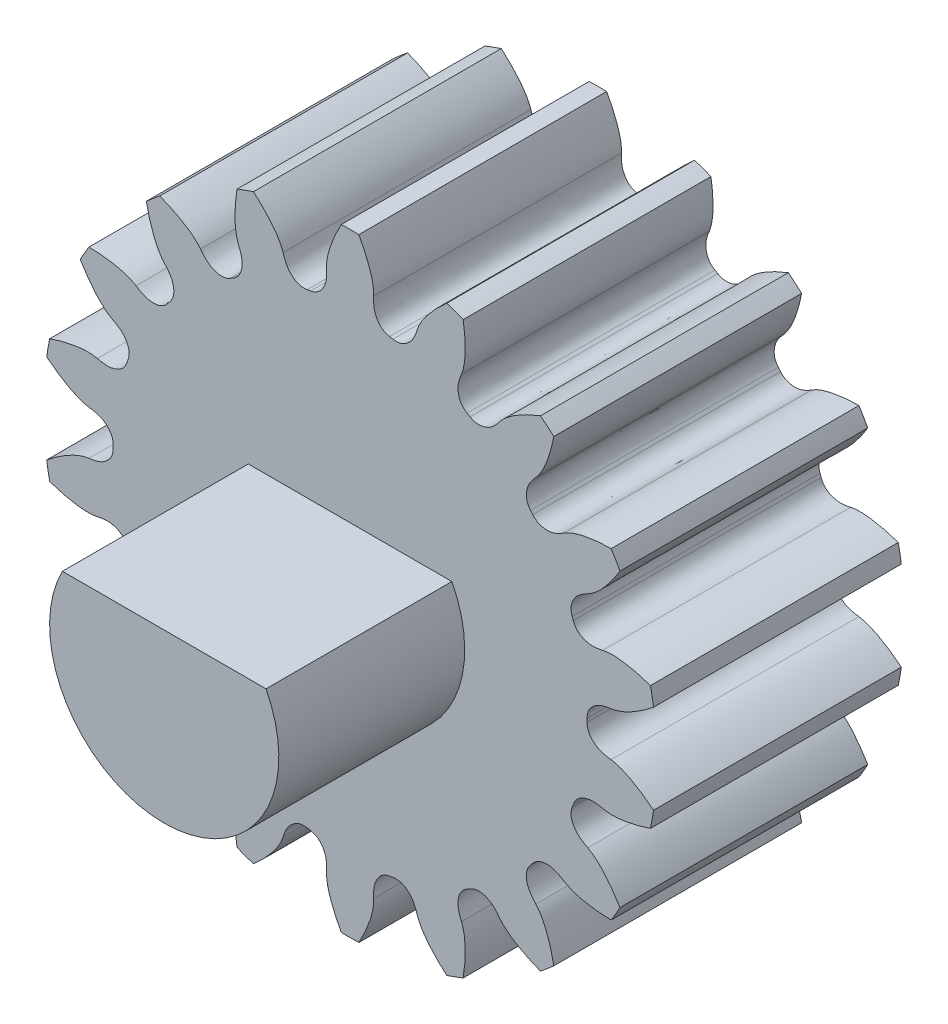
SolidWorks part; units mm, degrees
ref_plane "Спереди" through (0, 0, 0) normal (0, 0, 1) x (1, 0, 0)
ref_plane "Сверху" through (0, 0, 0) normal (0, 1, 0) x (1, 0, 0)
ref_plane "Справа" through (0, 0, 0) normal (1, 0, 0) x (0, 0, -1)
sketch "Sketch1" plane through (0, 0, 0) normal (0, 0, 1) x (1, 0, 0)
  circle A0 centre (0, 0) radius 5.5
extrude "Extrude1" add sketch "Sketch1" along normal blind 4
sketch "Sketch2" plane through (0, 0, 4) normal (0, 0, 1) x (1, 0, 0)
  line L0 (1.6432, 0.85) -> (-1.6432, 0.85)
  line L1 (1.7321, 1) -> (-1.7321, 1)
  arc A0 (-1.7321, 1) -> (1.7321, 1) centre (0, 0) ccw
  arc A1 (-1.6432, 0.85) -> (1.6432, 0.85) centre (0, 0) ccw
  dimension "D1" = 0.15
extrude "Extrude2" add sketch "Sketch2" along normal blind 3 contours L0 A1 region at (0, -0.3518, 4)
sketch "Sketch3" plane through (0, 0, 0) normal (0, 0, -1) x (-1, 0, 0)
  line L0 (1.1832, 1.15) -> (-1.1832, 1.15)
  line L1 (1.118, 1) -> (-1.118, 1)
  arc A0 (-1.118, 1) -> (1.118, 1) centre (0, 0) ccw
  arc A1 (-1.1832, 1.15) -> (1.1832, 1.15) centre (0, 0) ccw
  dimension "D1" = 0.15
extrude "Extrude3" cut sketch "Sketch3" against normal blind 3.5 contours L1 A0 | A0 L1 | L0 A1 A0 L1 region at (0, -1.6067, 0) region at (0, -0.148, 0)
sketch "Sketch4" plane through (0, 0, 0) normal (0, 0, 1) x (1, 0, 0)
  line L0 (0, 0) -> (0, 6.5) construction
  line L1 (0, 0) -> (0, -6.5) construction
  line L2 (0, 0) -> (-6.5, 0) construction
  line L3 (0, 0) -> (6.5, 0) construction
  arc A28 (-0.6456, 3.8208) -> (-0.7002, 3.8112) centre (0, 0) ccw
  arc A30 (-1.549, 4.754) -> (-1.8692, 4.6375) centre (0, 0) ccw
  arc A31 (-1.9135, 3.3696) -> (-1.9614, 3.3419) centre (0, 0) ccw
  arc A32 (-3.0816, 3.9375) -> (-3.3426, 3.7185) centre (0, 0) ccw
  arc A33 (-2.9505, 2.512) -> (-2.9862, 2.4695) centre (0, 0) ccw
  arc A34 (-4.2424, 2.6461) -> (-4.4128, 2.351) centre (0, 0) ccw
  arc A35 (-3.6317, 1.3513) -> (-3.6507, 1.2993) centre (0, 0) ccw
  arc A36 (-4.8916, 1.0355) -> (-4.9508, 0.6999) centre (0, 0) ccw
  arc A37 (-3.8749, 0.0277) -> (-3.8749, -0.0277) centre (0, 0) ccw
  arc A38 (-4.9508, -0.6999) -> (-4.8916, -1.0355) centre (0, 0) ccw
  arc A39 (-3.6507, -1.2993) -> (-3.6317, -1.3513) centre (0, 0) ccw
  arc A40 (-4.4128, -2.351) -> (-4.2424, -2.6461) centre (0, 0) ccw
  arc A41 (-2.9862, -2.4695) -> (-2.9505, -2.512) centre (0, 0) ccw
  arc A42 (-3.3426, -3.7185) -> (-3.0816, -3.9375) centre (0, 0) ccw
  arc A43 (-1.9614, -3.3419) -> (-1.9135, -3.3696) centre (0, 0) ccw
  arc A44 (-1.8692, -4.6375) -> (-1.549, -4.754) centre (0, 0) ccw
  arc A45 (-0.7002, -3.8112) -> (-0.6456, -3.8208) centre (0, 0) ccw
  arc A46 (-0.1704, -4.9971) -> (0.1704, -4.9971) centre (0, 0) ccw
  arc A47 (0.6456, -3.8208) -> (0.7002, -3.8112) centre (0, 0) ccw
  arc A48 (1.549, -4.754) -> (1.8692, -4.6375) centre (0, 0) ccw
  arc A49 (1.9135, -3.3696) -> (1.9614, -3.3419) centre (0, 0) ccw
  arc A50 (3.0816, -3.9375) -> (3.3426, -3.7185) centre (0, 0) ccw
  arc A51 (2.9505, -2.512) -> (2.9862, -2.4695) centre (0, 0) ccw
  arc A52 (4.2424, -2.6461) -> (4.4128, -2.351) centre (0, 0) ccw
  arc A53 (3.6317, -1.3513) -> (3.6507, -1.2993) centre (0, 0) ccw
  arc A54 (4.8916, -1.0355) -> (4.9508, -0.6999) centre (0, 0) ccw
  arc A55 (3.8749, -0.0277) -> (3.8749, 0.0277) centre (0, 0) ccw
  arc A56 (4.9508, 0.6999) -> (4.8916, 1.0355) centre (0, 0) ccw
  arc A57 (3.6507, 1.2993) -> (3.6317, 1.3513) centre (0, 0) ccw
  arc A58 (4.4128, 2.351) -> (4.2424, 2.6461) centre (0, 0) ccw
  arc A59 (2.9862, 2.4695) -> (2.9505, 2.512) centre (0, 0) ccw
  arc A60 (3.3426, 3.7185) -> (3.0816, 3.9375) centre (0, 0) ccw
  arc A61 (1.9614, 3.3419) -> (1.9135, 3.3696) centre (0, 0) ccw
  arc A62 (1.8692, 4.6375) -> (1.549, 4.754) centre (0, 0) ccw
  arc A63 (0.7002, 3.8112) -> (0.6456, 3.8208) centre (0, 0) ccw
  arc A65 (0.1704, 4.9971) -> (-0.1704, 4.9971) centre (0, 0) ccw
  circle A66 centre (0, 0) radius 6.3388
  arc A67 (-0.6372, 3.7715) -> (-0.6912, 3.762) centre (0, 0) ccw
  arc A68 (-1.5598, 4.6978) -> (-1.8248, 4.6014) centre (0, 0) ccw
  arc A69 (-1.8887, 3.3262) -> (-1.9362, 3.2988) centre (0, 0) ccw
  arc A70 (-3.0725, 3.881) -> (-3.2885, 3.6997) centre (0, 0) ccw
  arc A71 (-2.9124, 2.4796) -> (-2.9476, 2.4376) centre (0, 0) ccw
  arc A72 (-4.2146, 2.5961) -> (-4.3556, 2.3519) centre (0, 0) ccw
  arc A73 (-3.5849, 1.3339) -> (-3.6036, 1.2825) centre (0, 0) ccw
  arc A74 (-4.8483, 0.9981) -> (-4.8973, 0.7203) centre (0, 0) ccw
  arc A75 (-3.8249, 0.0274) -> (-3.8249, -0.0274) centre (0, 0) ccw
  arc A76 (-4.8973, -0.7203) -> (-4.8483, -0.9981) centre (0, 0) ccw
  arc A77 (-3.6036, -1.2825) -> (-3.5849, -1.3339) centre (0, 0) ccw
  arc A78 (-4.3556, -2.3519) -> (-4.2146, -2.5961) centre (0, 0) ccw
  arc A79 (-2.9476, -2.4376) -> (-2.9124, -2.4796) centre (0, 0) ccw
  arc A80 (-3.2885, -3.6997) -> (-3.0725, -3.881) centre (0, 0) ccw
  arc A81 (-1.9362, -3.2988) -> (-1.8887, -3.3262) centre (0, 0) ccw
  arc A82 (-1.8248, -4.6014) -> (-1.5598, -4.6978) centre (0, 0) ccw
  arc A83 (-0.6912, -3.762) -> (-0.6372, -3.7715) centre (0, 0) ccw
  arc A84 (-0.141, -4.948) -> (0.141, -4.948) centre (0, 0) ccw
  arc A85 (0.6372, -3.7715) -> (0.6912, -3.762) centre (0, 0) ccw
  arc A86 (1.5598, -4.6978) -> (1.8248, -4.6014) centre (0, 0) ccw
  arc A87 (1.8887, -3.3262) -> (1.9362, -3.2988) centre (0, 0) ccw
  arc A88 (3.0725, -3.881) -> (3.2885, -3.6997) centre (0, 0) ccw
  arc A89 (2.9124, -2.4796) -> (2.9476, -2.4376) centre (0, 0) ccw
  arc A90 (4.2146, -2.5961) -> (4.3556, -2.3519) centre (0, 0) ccw
  arc A91 (3.5849, -1.3339) -> (3.6036, -1.2825) centre (0, 0) ccw
  arc A92 (4.8483, -0.9981) -> (4.8973, -0.7203) centre (0, 0) ccw
  arc A93 (3.8249, -0.0274) -> (3.8249, 0.0274) centre (0, 0) ccw
  arc A94 (4.8973, 0.7203) -> (4.8483, 0.9981) centre (0, 0) ccw
  arc A95 (3.6036, 1.2825) -> (3.5849, 1.3339) centre (0, 0) ccw
  arc A96 (4.3556, 2.3519) -> (4.2146, 2.5961) centre (0, 0) ccw
  arc A97 (2.9476, 2.4376) -> (2.9124, 2.4796) centre (0, 0) ccw
  arc A98 (3.2885, 3.6997) -> (3.0725, 3.881) centre (0, 0) ccw
  arc A99 (1.9362, 3.2988) -> (1.8887, 3.3262) centre (0, 0) ccw
  arc A100 (1.8248, 4.6014) -> (1.5598, 4.6978) centre (0, 0) ccw
  arc A101 (0.6912, 3.762) -> (0.6372, 3.7715) centre (0, 0) ccw
  arc A102 (0.141, 4.948) -> (-0.141, 4.948) centre (0, 0) ccw
  spline S0 degree 3 poles (0.4314, 4.2073) (0.4264, 4.1628) (0.4271, 4.1189) (0.4335, 4.0758) (0.4372, 4.0511) (0.4421, 4.026) (0.4501, 4.0023) (0.4558, 3.9851) (0.4628, 3.968) (0.4713, 3.952) (0.4783, 3.9388) (0.4864, 3.9259) (0.4954, 3.914) (0.5034, 3.9034) (0.5123, 3.8933) (0.5218, 3.8841) (0.5307, 3.8755) (0.5403, 3.8675) (0.5504, 3.8604) (0.56, 3.8536) (0.5702, 3.8474) (0.5807, 3.8421) (0.5909, 3.837) (0.6017, 3.8326) (0.6125, 3.829) (0.6233, 3.8255) (0.6343, 3.8228) (0.6456, 3.8208) knots 0 0 0 0 1 1 1 2 2 2 3 3 3 4 4 4 5 5 5 6 6 6 7 7 7 8 8 8 9 9 9 9
  spline S1 degree 3 poles (-0.4314, 4.2073) (-0.4264, 4.1628) (-0.4271, 4.1189) (-0.4335, 4.0758) (-0.4372, 4.0511) (-0.4421, 4.026) (-0.4501, 4.0023) (-0.4558, 3.9851) (-0.4628, 3.968) (-0.4713, 3.952) (-0.4783, 3.9388) (-0.4864, 3.9259) (-0.4954, 3.914) (-0.5034, 3.9034) (-0.5123, 3.8933) (-0.5218, 3.8841) (-0.5307, 3.8755) (-0.5403, 3.8675) (-0.5504, 3.8604) (-0.56, 3.8536) (-0.5702, 3.8474) (-0.5807, 3.8421) (-0.5909, 3.837) (-0.6017, 3.8326) (-0.6125, 3.829) (-0.6233, 3.8255) (-0.6343, 3.8228) (-0.6456, 3.8208) knots 0 0 0 0 1 1 1 2 2 2 3 3 3 4 4 4 5 5 5 6 6 6 7 7 7 8 8 8 9 9 9 9
  spline S2 degree 3 poles (0.4314, 4.2073) (0.432, 4.2362) (0.431, 4.265) (0.4284, 4.2936) (0.4258, 4.3229) (0.4209, 4.352) (0.4156, 4.3809) (0.4101, 4.4104) (0.4034, 4.4397) (0.3959, 4.4687) (0.3884, 4.4983) (0.3797, 4.5277) (0.3705, 4.5568) (0.361, 4.5865) (0.3507, 4.6159) (0.3398, 4.6451) (0.3287, 4.6748) (0.3167, 4.7042) (0.3042, 4.7333) (0.2915, 4.763) (0.278, 4.7924) (0.264, 4.8215) (0.2497, 4.8511) (0.2348, 4.8805) (0.2193, 4.9095) (0.2036, 4.939) (0.1873, 4.9682) (0.1704, 4.9971) knots 0 0 0 0 1 1 1 2 2 2 3 3 3 4 4 4 5 5 5 6 6 6 7 7 7 8 8 8 9 9 9 9
  spline S3 degree 3 poles (-0.4314, 4.2073) (-0.432, 4.2362) (-0.431, 4.265) (-0.4284, 4.2936) (-0.4258, 4.3229) (-0.4209, 4.352) (-0.4156, 4.3809) (-0.4101, 4.4104) (-0.4034, 4.4397) (-0.3959, 4.4687) (-0.3884, 4.4983) (-0.3797, 4.5277) (-0.3705, 4.5568) (-0.361, 4.5865) (-0.3507, 4.6159) (-0.3398, 4.6451) (-0.3287, 4.6748) (-0.3167, 4.7042) (-0.3042, 4.7333) (-0.2915, 4.763) (-0.278, 4.7924) (-0.264, 4.8215) (-0.2497, 4.8511) (-0.2348, 4.8805) (-0.2193, 4.9095) (-0.2036, 4.939) (-0.1873, 4.9682) (-0.1704, 4.9971) knots 0 0 0 0 1 1 1 2 2 2 3 3 3 4 4 4 5 5 5 6 6 6 7 7 7 8 8 8 9 9 9 9
  spline S4 degree 3 poles (-1.0336, 4.1011) (-1.0231, 4.0576) (-1.0074, 4.0166) (-0.9866, 3.9783) (-0.9747, 3.9563) (-0.9616, 3.9344) (-0.9459, 3.9148) (-0.9346, 3.9007) (-0.9223, 3.887) (-0.9088, 3.8748) (-0.8977, 3.8649) (-0.8857, 3.8555) (-0.8732, 3.8474) (-0.862, 3.8402) (-0.8502, 3.8337) (-0.8381, 3.8283) (-0.8268, 3.8233) (-0.8151, 3.819) (-0.8032, 3.8158) (-0.7918, 3.8127) (-0.7801, 3.8104) (-0.7684, 3.809) (-0.757, 3.8077) (-0.7454, 3.8072) (-0.734, 3.8076) (-0.7227, 3.808) (-0.7114, 3.8092) (-0.7002, 3.8112) knots 0 0 0 0 1 1 1 2 2 2 3 3 3 4 4 4 5 5 5 6 6 6 7 7 7 8 8 8 9 9 9 9
  spline S5 degree 3 poles (-1.8443, 3.806) (-1.8244, 3.7659) (-1.8101, 3.7245) (-1.8014, 3.6817) (-1.7963, 3.6572) (-1.7924, 3.632) (-1.7918, 3.607) (-1.7913, 3.5888) (-1.792, 3.5704) (-1.7945, 3.5525) (-1.7966, 3.5377) (-1.7998, 3.5228) (-1.8042, 3.5085) (-1.8081, 3.4958) (-1.813, 3.4833) (-1.8188, 3.4714) (-1.8242, 3.4603) (-1.8305, 3.4495) (-1.8375, 3.4393) (-1.8442, 3.4297) (-1.8517, 3.4204) (-1.8598, 3.4118) (-1.8676, 3.4035) (-1.8762, 3.3956) (-1.8852, 3.3886) (-1.8941, 3.3816) (-1.9035, 3.3753) (-1.9135, 3.3696) knots 0 0 0 0 1 1 1 2 2 2 3 3 3 4 4 4 5 5 5 6 6 6 7 7 7 8 8 8 9 9 9 9
  spline S6 degree 3 poles (-1.0336, 4.1011) (-1.043, 4.1285) (-1.0537, 4.1552) (-1.066, 4.1812) (-1.0784, 4.2078) (-1.093, 4.2335) (-1.1079, 4.2588) (-1.123, 4.2847) (-1.1394, 4.3099) (-1.1563, 4.3346) (-1.1736, 4.3599) (-1.1917, 4.3845) (-1.2104, 4.4087) (-1.2294, 4.4334) (-1.2492, 4.4575) (-1.2694, 4.4811) (-1.29, 4.5052) (-1.3113, 4.5288) (-1.333, 4.5519) (-1.3551, 4.5755) (-1.3779, 4.5985) (-1.401, 4.621) (-1.4245, 4.644) (-1.4486, 4.6664) (-1.473, 4.6884) (-1.4979, 4.7108) (-1.5232, 4.7326) (-1.549, 4.754) knots 0 0 0 0 1 1 1 2 2 2 3 3 3 4 4 4 5 5 5 6 6 6 7 7 7 8 8 8 9 9 9 9
  spline S7 degree 3 poles (-1.8443, 3.806) (-1.8548, 3.833) (-1.8637, 3.8604) (-1.8711, 3.8882) (-1.8786, 3.9166) (-1.884, 3.9456) (-1.8889, 3.9746) (-1.8938, 4.0041) (-1.8975, 4.034) (-1.9004, 4.0638) (-1.9034, 4.0942) (-1.9054, 4.1248) (-1.9067, 4.1553) (-1.9079, 4.1864) (-1.9083, 4.2176) (-1.908, 4.2487) (-1.9077, 4.2804) (-1.9065, 4.3122) (-1.9048, 4.3438) (-1.903, 4.3761) (-1.9004, 4.4083) (-1.8971, 4.4404) (-1.8939, 4.4732) (-1.8899, 4.5058) (-1.8853, 4.5384) (-1.8806, 4.5715) (-1.8752, 4.6045) (-1.8692, 4.6375) knots 0 0 0 0 1 1 1 2 2 2 3 3 3 4 4 4 5 5 5 6 6 6 7 7 7 8 8 8 9 9 9 9
  spline S8 degree 3 poles (-2.3739, 3.5002) (-2.3491, 3.463) (-2.3204, 3.4298) (-2.2878, 3.4009) (-2.2691, 3.3843) (-2.2492, 3.3682) (-2.2278, 3.3552) (-2.2124, 3.3458) (-2.1961, 3.3371) (-2.1792, 3.3303) (-2.1654, 3.3248) (-2.151, 3.32) (-2.1364, 3.3167) (-2.1234, 3.3138) (-2.1101, 3.3117) (-2.0969, 3.3108) (-2.0846, 3.3099) (-2.0721, 3.31) (-2.0598, 3.311) (-2.0481, 3.312) (-2.0363, 3.3138) (-2.0248, 3.3165) (-2.0137, 3.3191) (-2.0026, 3.3226) (-1.992, 3.3269) (-1.9815, 3.3311) (-1.9713, 3.3361) (-1.9614, 3.3419) knots 0 0 0 0 1 1 1 2 2 2 3 3 3 4 4 4 5 5 5 6 6 6 7 7 7 8 8 8 9 9 9 9
  spline S9 degree 3 poles (-3.0348, 2.9457) (-3.0024, 2.9148) (-2.9748, 2.8807) (-2.952, 2.8436) (-2.9389, 2.8223) (-2.9265, 2.7999) (-2.9174, 2.7766) (-2.9108, 2.7597) (-2.9051, 2.7422) (-2.9013, 2.7245) (-2.8982, 2.7098) (-2.8961, 2.6948) (-2.8954, 2.6799) (-2.8947, 2.6666) (-2.895, 2.6531) (-2.8964, 2.6399) (-2.8977, 2.6277) (-2.8999, 2.6154) (-2.903, 2.6035) (-2.906, 2.5921) (-2.9098, 2.5808) (-2.9145, 2.57) (-2.919, 2.5595) (-2.9244, 2.5492) (-2.9305, 2.5394) (-2.9364, 2.5298) (-2.9431, 2.5207) (-2.9505, 2.512) knots 0 0 0 0 1 1 1 2 2 2 3 3 3 4 4 4 5 5 5 6 6 6 7 7 7 8 8 8 9 9 9 9
  spline S10 degree 3 poles (-2.3739, 3.5002) (-2.3921, 3.5228) (-2.4113, 3.5442) (-2.4317, 3.5645) (-2.4525, 3.5852) (-2.475, 3.6044) (-2.4977, 3.6231) (-2.5208, 3.6422) (-2.5448, 3.6603) (-2.5691, 3.6777) (-2.594, 3.6955) (-2.6195, 3.7125) (-2.6453, 3.7289) (-2.6716, 3.7455) (-2.6984, 3.7614) (-2.7255, 3.7767) (-2.7531, 3.7923) (-2.7812, 3.8072) (-2.8095, 3.8215) (-2.8383, 3.836) (-2.8675, 3.8499) (-2.897, 3.8632) (-2.9269, 3.8767) (-2.9572, 3.8896) (-2.9877, 3.9019) (-3.0187, 3.9144) (-3.05, 3.9263) (-3.0816, 3.9375) knots 0 0 0 0 1 1 1 2 2 2 3 3 3 4 4 4 5 5 5 6 6 6 7 7 7 8 8 8 9 9 9 9
  spline S11 degree 3 poles (-3.0348, 2.9457) (-3.0539, 2.9675) (-3.0716, 2.9902) (-3.0881, 3.0137) (-3.1049, 3.0378) (-3.1199, 3.0633) (-3.1343, 3.0889) (-3.1491, 3.1149) (-3.1627, 3.1417) (-3.1757, 3.1687) (-3.189, 3.1963) (-3.2012, 3.2243) (-3.2129, 3.2526) (-3.2247, 3.2814) (-3.2357, 3.3106) (-3.2461, 3.3399) (-3.2566, 3.3698) (-3.2664, 3.4) (-3.2756, 3.4304) (-3.2849, 3.4613) (-3.2935, 3.4925) (-3.3015, 3.5238) (-3.3096, 3.5557) (-3.317, 3.5877) (-3.3238, 3.6199) (-3.3307, 3.6526) (-3.337, 3.6855) (-3.3426, 3.7185) knots 0 0 0 0 1 1 1 2 2 2 3 3 3 4 4 4 5 5 5 6 6 6 7 7 7 8 8 8 9 9 9 9
  spline S12 degree 3 poles (-3.4279, 2.4772) (-3.3919, 2.4507) (-3.3535, 2.4294) (-3.313, 2.4133) (-3.2897, 2.4041) (-3.2656, 2.3958) (-3.241, 2.3909) (-3.2233, 2.3873) (-3.205, 2.3848) (-3.1869, 2.3842) (-3.1719, 2.3837) (-3.1568, 2.3841) (-3.1419, 2.386) (-3.1288, 2.3877) (-3.1155, 2.3903) (-3.1028, 2.3939) (-3.0909, 2.3974) (-3.0792, 2.4017) (-3.068, 2.4068) (-3.0573, 2.4117) (-3.0469, 2.4175) (-3.037, 2.424) (-3.0275, 2.4303) (-3.0183, 2.4373) (-3.0097, 2.445) (-3.0013, 2.4525) (-2.9935, 2.4607) (-2.9862, 2.4695) knots 0 0 0 0 1 1 1 2 2 2 3 3 3 4 4 4 5 5 5 6 6 6 7 7 7 8 8 8 9 9 9 9
  spline S13 degree 3 poles (-3.8593, 1.7301) (-3.8183, 1.7121) (-3.7807, 1.6896) (-3.7465, 1.6625) (-3.7269, 1.6469) (-3.7076, 1.6301) (-3.6911, 1.6114) (-3.6791, 1.5978) (-3.6678, 1.5832) (-3.6582, 1.5678) (-3.6503, 1.5551) (-3.6431, 1.5418) (-3.6373, 1.528) (-3.6322, 1.5157) (-3.6278, 1.503) (-3.6246, 1.4901) (-3.6216, 1.4782) (-3.6195, 1.4658) (-3.6184, 1.4536) (-3.6173, 1.4419) (-3.617, 1.4299) (-3.6177, 1.4182) (-3.6184, 1.4067) (-3.6199, 1.3952) (-3.6223, 1.384) (-3.6246, 1.373) (-3.6278, 1.3621) (-3.6317, 1.3513) knots 0 0 0 0 1 1 1 2 2 2 3 3 3 4 4 4 5 5 5 6 6 6 7 7 7 8 8 8 9 9 9 9
  spline S14 degree 3 poles (-3.4279, 2.4772) (-3.4527, 2.4922) (-3.4781, 2.5057) (-3.5042, 2.5178) (-3.5308, 2.5302) (-3.5585, 2.5405) (-3.5862, 2.5504) (-3.6144, 2.5604) (-3.6432, 2.5691) (-3.6721, 2.5772) (-3.7015, 2.5855) (-3.7312, 2.5927) (-3.7611, 2.5992) (-3.7915, 2.6059) (-3.8221, 2.6117) (-3.8529, 2.6168) (-3.8841, 2.622) (-3.9156, 2.6264) (-3.9471, 2.6301) (-3.9792, 2.6339) (-4.0113, 2.637) (-4.0436, 2.6394) (-4.0763, 2.6419) (-4.1092, 2.6436) (-4.1421, 2.6447) (-4.1755, 2.6458) (-4.2089, 2.6463) (-4.2424, 2.6461) knots 0 0 0 0 1 1 1 2 2 2 3 3 3 4 4 4 5 5 5 6 6 6 7 7 7 8 8 8 9 9 9 9
  spline S15 degree 3 poles (-3.8593, 1.7301) (-3.8846, 1.744) (-3.9091, 1.7593) (-3.9326, 1.7758) (-3.9566, 1.7927) (-3.9794, 1.8115) (-4.0018, 1.8306) (-4.0246, 1.85) (-4.0465, 1.8705) (-4.068, 1.8915) (-4.0898, 1.9128) (-4.111, 1.935) (-4.1316, 1.9576) (-4.1525, 1.9806) (-4.1729, 2.0042) (-4.1926, 2.0283) (-4.2128, 2.0528) (-4.2323, 2.0778) (-4.2513, 2.1032) (-4.2706, 2.1291) (-4.2894, 2.1554) (-4.3076, 2.1821) (-4.3261, 2.2093) (-4.344, 2.2369) (-4.3614, 2.2648) (-4.3791, 2.2932) (-4.3962, 2.3219) (-4.4128, 2.351) knots 0 0 0 0 1 1 1 2 2 2 3 3 3 4 4 4 5 5 5 6 6 6 7 7 7 8 8 8 9 9 9 9
  spline S16 degree 3 poles (-4.0684, 1.1554) (-4.0255, 1.1428) (-3.9822, 1.1359) (-3.9386, 1.1347) (-3.9136, 1.134) (-3.888, 1.1345) (-3.8633, 1.1382) (-3.8454, 1.1409) (-3.8273, 1.1448) (-3.8101, 1.1504) (-3.7959, 1.155) (-3.7818, 1.1607) (-3.7685, 1.1675) (-3.7567, 1.1736) (-3.7452, 1.1806) (-3.7344, 1.1884) (-3.7245, 1.1956) (-3.7149, 1.2037) (-3.7062, 1.2123) (-3.6978, 1.2206) (-3.69, 1.2296) (-3.6829, 1.239) (-3.6761, 1.2482) (-3.6699, 1.258) (-3.6645, 1.2681) (-3.6591, 1.2781) (-3.6545, 1.2885) (-3.6507, 1.2993) knots 0 0 0 0 1 1 1 2 2 2 3 3 3 4 4 4 5 5 5 6 6 6 7 7 7 8 8 8 9 9 9 9
  spline S17 degree 3 poles (-4.2183, 0.3058) (-4.1736, 0.3029) (-4.1305, 0.2946) (-4.0892, 0.2808) (-4.0654, 0.2729) (-4.0416, 0.2637) (-4.0196, 0.2518) (-4.0037, 0.2431) (-3.9881, 0.2333) (-3.9738, 0.2221) (-3.962, 0.2129) (-3.9507, 0.2028) (-3.9406, 0.1918) (-3.9315, 0.1821) (-3.9231, 0.1716) (-3.9157, 0.1606) (-3.9088, 0.1503) (-3.9026, 0.1395) (-3.8973, 0.1284) (-3.8923, 0.1177) (-3.888, 0.1066) (-3.8846, 0.0953) (-3.8813, 0.0843) (-3.8788, 0.073) (-3.8772, 0.0617) (-3.8756, 0.0505) (-3.8748, 0.0391) (-3.8749, 0.0277) knots 0 0 0 0 1 1 1 2 2 2 3 3 3 4 4 4 5 5 5 6 6 6 7 7 7 8 8 8 9 9 9 9
  spline S18 degree 3 poles (-4.0684, 1.1554) (-4.0968, 1.161) (-4.1254, 1.165) (-4.154, 1.1675) (-4.1833, 1.17) (-4.2128, 1.1702) (-4.2422, 1.17) (-4.2722, 1.1698) (-4.3022, 1.1682) (-4.3321, 1.1659) (-4.3625, 1.1636) (-4.393, 1.1602) (-4.4232, 1.1561) (-4.4541, 1.152) (-4.4849, 1.1469) (-4.5155, 1.1412) (-4.5467, 1.1354) (-4.5777, 1.1288) (-4.6086, 1.1215) (-4.64, 1.1141) (-4.6713, 1.106) (-4.7024, 1.0972) (-4.7341, 1.0883) (-4.7655, 1.0787) (-4.7968, 1.0685) (-4.8286, 1.0582) (-4.8602, 1.0472) (-4.8916, 1.0355) knots 0 0 0 0 1 1 1 2 2 2 3 3 3 4 4 4 5 5 5 6 6 6 7 7 7 8 8 8 9 9 9 9
  spline S19 degree 3 poles (-4.2183, 0.3058) (-4.2468, 0.3102) (-4.275, 0.3162) (-4.3028, 0.3237) (-4.3311, 0.3314) (-4.359, 0.3412) (-4.3865, 0.3515) (-4.4146, 0.362) (-4.4423, 0.3737) (-4.4696, 0.3861) (-4.4974, 0.3987) (-4.5248, 0.4123) (-4.5519, 0.4264) (-4.5795, 0.4409) (-4.6067, 0.4562) (-4.6335, 0.472) (-4.6608, 0.4881) (-4.6877, 0.505) (-4.7143, 0.5223) (-4.7413, 0.54) (-4.7679, 0.5584) (-4.7941, 0.5773) (-4.8208, 0.5964) (-4.8471, 0.6162) (-4.873, 0.6365) (-4.8993, 0.6571) (-4.9252, 0.6783) (-4.9508, 0.6999) knots 0 0 0 0 1 1 1 2 2 2 3 3 3 4 4 4 5 5 5 6 6 6 7 7 7 8 8 8 9 9 9 9
  spline S20 degree 3 poles (-4.2183, -0.3058) (-4.1736, -0.3029) (-4.1305, -0.2946) (-4.0892, -0.2808) (-4.0654, -0.2729) (-4.0416, -0.2637) (-4.0196, -0.2518) (-4.0037, -0.2431) (-3.9881, -0.2333) (-3.9738, -0.2221) (-3.962, -0.2129) (-3.9507, -0.2028) (-3.9406, -0.1918) (-3.9315, -0.1821) (-3.9231, -0.1716) (-3.9157, -0.1606) (-3.9088, -0.1503) (-3.9026, -0.1395) (-3.8973, -0.1284) (-3.8923, -0.1177) (-3.888, -0.1066) (-3.8846, -0.0953) (-3.8813, -0.0843) (-3.8788, -0.073) (-3.8772, -0.0617) (-3.8756, -0.0505) (-3.8748, -0.0391) (-3.8749, -0.0277) knots 0 0 0 0 1 1 1 2 2 2 3 3 3 4 4 4 5 5 5 6 6 6 7 7 7 8 8 8 9 9 9 9
  spline S21 degree 3 poles (-4.0684, -1.1554) (-4.0255, -1.1428) (-3.9822, -1.1359) (-3.9386, -1.1347) (-3.9136, -1.134) (-3.888, -1.1345) (-3.8633, -1.1382) (-3.8454, -1.1409) (-3.8273, -1.1448) (-3.8101, -1.1504) (-3.7959, -1.155) (-3.7818, -1.1607) (-3.7685, -1.1675) (-3.7567, -1.1736) (-3.7452, -1.1806) (-3.7344, -1.1884) (-3.7245, -1.1956) (-3.7149, -1.2037) (-3.7062, -1.2123) (-3.6978, -1.2206) (-3.69, -1.2296) (-3.6829, -1.239) (-3.6761, -1.2482) (-3.6699, -1.258) (-3.6645, -1.2681) (-3.6591, -1.2781) (-3.6545, -1.2885) (-3.6507, -1.2993) knots 0 0 0 0 1 1 1 2 2 2 3 3 3 4 4 4 5 5 5 6 6 6 7 7 7 8 8 8 9 9 9 9
  spline S22 degree 3 poles (-4.2183, -0.3058) (-4.2468, -0.3102) (-4.275, -0.3162) (-4.3028, -0.3237) (-4.3311, -0.3314) (-4.359, -0.3412) (-4.3865, -0.3515) (-4.4146, -0.362) (-4.4423, -0.3737) (-4.4696, -0.3861) (-4.4974, -0.3987) (-4.5248, -0.4123) (-4.5519, -0.4264) (-4.5795, -0.4409) (-4.6067, -0.4562) (-4.6335, -0.472) (-4.6608, -0.4881) (-4.6877, -0.505) (-4.7143, -0.5223) (-4.7413, -0.54) (-4.7679, -0.5584) (-4.7941, -0.5773) (-4.8208, -0.5964) (-4.8471, -0.6162) (-4.873, -0.6365) (-4.8993, -0.6571) (-4.9252, -0.6783) (-4.9508, -0.6999) knots 0 0 0 0 1 1 1 2 2 2 3 3 3 4 4 4 5 5 5 6 6 6 7 7 7 8 8 8 9 9 9 9
  spline S23 degree 3 poles (-4.0684, -1.1554) (-4.0968, -1.161) (-4.1254, -1.165) (-4.154, -1.1675) (-4.1833, -1.17) (-4.2128, -1.1702) (-4.2422, -1.17) (-4.2722, -1.1698) (-4.3022, -1.1682) (-4.3321, -1.1659) (-4.3625, -1.1636) (-4.393, -1.1602) (-4.4232, -1.1561) (-4.4541, -1.152) (-4.4849, -1.1469) (-4.5155, -1.1412) (-4.5467, -1.1354) (-4.5777, -1.1288) (-4.6086, -1.1215) (-4.64, -1.1141) (-4.6713, -1.106) (-4.7024, -1.0972) (-4.7341, -1.0883) (-4.7655, -1.0787) (-4.7968, -1.0685) (-4.8286, -1.0582) (-4.8602, -1.0472) (-4.8916, -1.0355) knots 0 0 0 0 1 1 1 2 2 2 3 3 3 4 4 4 5 5 5 6 6 6 7 7 7 8 8 8 9 9 9 9
  spline S24 degree 3 poles (-3.8593, -1.7301) (-3.8183, -1.7121) (-3.7807, -1.6896) (-3.7465, -1.6625) (-3.7269, -1.6469) (-3.7076, -1.6301) (-3.6911, -1.6114) (-3.6791, -1.5978) (-3.6678, -1.5832) (-3.6582, -1.5678) (-3.6503, -1.5551) (-3.6431, -1.5418) (-3.6373, -1.528) (-3.6322, -1.5157) (-3.6278, -1.503) (-3.6246, -1.4901) (-3.6216, -1.4782) (-3.6195, -1.4658) (-3.6184, -1.4536) (-3.6173, -1.4419) (-3.617, -1.4299) (-3.6177, -1.4182) (-3.6184, -1.4067) (-3.6199, -1.3952) (-3.6223, -1.384) (-3.6246, -1.373) (-3.6278, -1.3621) (-3.6317, -1.3513) knots 0 0 0 0 1 1 1 2 2 2 3 3 3 4 4 4 5 5 5 6 6 6 7 7 7 8 8 8 9 9 9 9
  spline S25 degree 3 poles (-3.4279, -2.4772) (-3.3919, -2.4507) (-3.3535, -2.4294) (-3.313, -2.4133) (-3.2897, -2.4041) (-3.2656, -2.3958) (-3.241, -2.3909) (-3.2233, -2.3873) (-3.205, -2.3848) (-3.1869, -2.3842) (-3.1719, -2.3837) (-3.1568, -2.3841) (-3.1419, -2.386) (-3.1288, -2.3877) (-3.1155, -2.3903) (-3.1028, -2.3939) (-3.0909, -2.3974) (-3.0792, -2.4017) (-3.068, -2.4068) (-3.0573, -2.4117) (-3.0469, -2.4175) (-3.037, -2.424) (-3.0275, -2.4303) (-3.0183, -2.4373) (-3.0097, -2.445) (-3.0013, -2.4525) (-2.9935, -2.4607) (-2.9862, -2.4695) knots 0 0 0 0 1 1 1 2 2 2 3 3 3 4 4 4 5 5 5 6 6 6 7 7 7 8 8 8 9 9 9 9
  spline S26 degree 3 poles (-3.8593, -1.7301) (-3.8846, -1.744) (-3.9091, -1.7593) (-3.9326, -1.7758) (-3.9566, -1.7927) (-3.9794, -1.8115) (-4.0018, -1.8306) (-4.0246, -1.85) (-4.0465, -1.8705) (-4.068, -1.8915) (-4.0898, -1.9128) (-4.111, -1.935) (-4.1316, -1.9576) (-4.1525, -1.9806) (-4.1729, -2.0042) (-4.1926, -2.0283) (-4.2128, -2.0528) (-4.2323, -2.0778) (-4.2513, -2.1032) (-4.2706, -2.1291) (-4.2894, -2.1554) (-4.3076, -2.1821) (-4.3261, -2.2093) (-4.344, -2.2369) (-4.3614, -2.2648) (-4.3791, -2.2932) (-4.3962, -2.3219) (-4.4128, -2.351) knots 0 0 0 0 1 1 1 2 2 2 3 3 3 4 4 4 5 5 5 6 6 6 7 7 7 8 8 8 9 9 9 9
  spline S27 degree 3 poles (-3.4279, -2.4772) (-3.4527, -2.4922) (-3.4781, -2.5057) (-3.5042, -2.5178) (-3.5308, -2.5302) (-3.5585, -2.5405) (-3.5862, -2.5504) (-3.6144, -2.5604) (-3.6432, -2.5691) (-3.6721, -2.5772) (-3.7015, -2.5855) (-3.7312, -2.5927) (-3.7611, -2.5992) (-3.7915, -2.6059) (-3.8221, -2.6117) (-3.8529, -2.6168) (-3.8841, -2.622) (-3.9156, -2.6264) (-3.9471, -2.6301) (-3.9792, -2.6339) (-4.0113, -2.637) (-4.0436, -2.6394) (-4.0763, -2.6419) (-4.1092, -2.6436) (-4.1421, -2.6447) (-4.1755, -2.6458) (-4.2089, -2.6463) (-4.2424, -2.6461) knots 0 0 0 0 1 1 1 2 2 2 3 3 3 4 4 4 5 5 5 6 6 6 7 7 7 8 8 8 9 9 9 9
  spline S28 degree 3 poles (-3.0348, -2.9457) (-3.0024, -2.9148) (-2.9748, -2.8807) (-2.952, -2.8436) (-2.9389, -2.8223) (-2.9265, -2.7999) (-2.9174, -2.7766) (-2.9108, -2.7597) (-2.9051, -2.7422) (-2.9013, -2.7245) (-2.8982, -2.7098) (-2.8961, -2.6948) (-2.8954, -2.6799) (-2.8947, -2.6666) (-2.895, -2.6531) (-2.8964, -2.6399) (-2.8977, -2.6277) (-2.8999, -2.6154) (-2.903, -2.6035) (-2.906, -2.5921) (-2.9098, -2.5808) (-2.9145, -2.57) (-2.919, -2.5595) (-2.9244, -2.5492) (-2.9305, -2.5394) (-2.9364, -2.5298) (-2.9431, -2.5207) (-2.9505, -2.512) knots 0 0 0 0 1 1 1 2 2 2 3 3 3 4 4 4 5 5 5 6 6 6 7 7 7 8 8 8 9 9 9 9
  spline S29 degree 3 poles (-2.3739, -3.5002) (-2.3491, -3.463) (-2.3204, -3.4298) (-2.2878, -3.4009) (-2.2691, -3.3843) (-2.2492, -3.3682) (-2.2278, -3.3552) (-2.2124, -3.3458) (-2.1961, -3.3371) (-2.1792, -3.3303) (-2.1654, -3.3248) (-2.151, -3.32) (-2.1364, -3.3167) (-2.1234, -3.3138) (-2.1101, -3.3117) (-2.0969, -3.3108) (-2.0846, -3.3099) (-2.0721, -3.31) (-2.0598, -3.311) (-2.0481, -3.312) (-2.0363, -3.3138) (-2.0248, -3.3165) (-2.0137, -3.3191) (-2.0026, -3.3226) (-1.992, -3.3269) (-1.9815, -3.3311) (-1.9713, -3.3361) (-1.9614, -3.3419) knots 0 0 0 0 1 1 1 2 2 2 3 3 3 4 4 4 5 5 5 6 6 6 7 7 7 8 8 8 9 9 9 9
  spline S30 degree 3 poles (-3.0348, -2.9457) (-3.0539, -2.9675) (-3.0716, -2.9902) (-3.0881, -3.0137) (-3.1049, -3.0378) (-3.1199, -3.0633) (-3.1343, -3.0889) (-3.1491, -3.1149) (-3.1627, -3.1417) (-3.1757, -3.1687) (-3.189, -3.1963) (-3.2012, -3.2243) (-3.2129, -3.2526) (-3.2247, -3.2814) (-3.2357, -3.3106) (-3.2461, -3.3399) (-3.2566, -3.3698) (-3.2664, -3.4) (-3.2756, -3.4304) (-3.2849, -3.4613) (-3.2935, -3.4925) (-3.3015, -3.5238) (-3.3096, -3.5557) (-3.317, -3.5877) (-3.3238, -3.6199) (-3.3307, -3.6526) (-3.337, -3.6855) (-3.3426, -3.7185) knots 0 0 0 0 1 1 1 2 2 2 3 3 3 4 4 4 5 5 5 6 6 6 7 7 7 8 8 8 9 9 9 9
  spline S31 degree 3 poles (-2.3739, -3.5002) (-2.3921, -3.5228) (-2.4113, -3.5442) (-2.4317, -3.5645) (-2.4525, -3.5852) (-2.475, -3.6044) (-2.4977, -3.6231) (-2.5208, -3.6422) (-2.5448, -3.6603) (-2.5691, -3.6777) (-2.594, -3.6955) (-2.6195, -3.7125) (-2.6453, -3.7289) (-2.6716, -3.7455) (-2.6984, -3.7614) (-2.7255, -3.7767) (-2.7531, -3.7923) (-2.7812, -3.8072) (-2.8095, -3.8215) (-2.8383, -3.836) (-2.8675, -3.8499) (-2.897, -3.8632) (-2.9269, -3.8767) (-2.9572, -3.8896) (-2.9877, -3.9019) (-3.0187, -3.9144) (-3.05, -3.9263) (-3.0816, -3.9375) knots 0 0 0 0 1 1 1 2 2 2 3 3 3 4 4 4 5 5 5 6 6 6 7 7 7 8 8 8 9 9 9 9
  spline S32 degree 3 poles (-1.8443, -3.806) (-1.8244, -3.7659) (-1.8101, -3.7245) (-1.8014, -3.6817) (-1.7963, -3.6572) (-1.7924, -3.632) (-1.7918, -3.607) (-1.7913, -3.5888) (-1.792, -3.5704) (-1.7945, -3.5525) (-1.7966, -3.5377) (-1.7998, -3.5228) (-1.8042, -3.5085) (-1.8081, -3.4958) (-1.813, -3.4833) (-1.8188, -3.4714) (-1.8242, -3.4603) (-1.8305, -3.4495) (-1.8375, -3.4393) (-1.8442, -3.4297) (-1.8517, -3.4204) (-1.8598, -3.4118) (-1.8676, -3.4035) (-1.8762, -3.3956) (-1.8852, -3.3886) (-1.8941, -3.3816) (-1.9035, -3.3753) (-1.9135, -3.3696) knots 0 0 0 0 1 1 1 2 2 2 3 3 3 4 4 4 5 5 5 6 6 6 7 7 7 8 8 8 9 9 9 9
  spline S33 degree 3 poles (-1.0336, -4.1011) (-1.0231, -4.0576) (-1.0074, -4.0166) (-0.9866, -3.9783) (-0.9747, -3.9563) (-0.9616, -3.9344) (-0.9459, -3.9148) (-0.9346, -3.9007) (-0.9223, -3.887) (-0.9088, -3.8748) (-0.8977, -3.8649) (-0.8857, -3.8555) (-0.8732, -3.8474) (-0.862, -3.8402) (-0.8502, -3.8337) (-0.8381, -3.8283) (-0.8268, -3.8233) (-0.8151, -3.819) (-0.8032, -3.8158) (-0.7918, -3.8127) (-0.7801, -3.8104) (-0.7684, -3.809) (-0.757, -3.8077) (-0.7454, -3.8072) (-0.734, -3.8076) (-0.7227, -3.808) (-0.7114, -3.8092) (-0.7002, -3.8112) knots 0 0 0 0 1 1 1 2 2 2 3 3 3 4 4 4 5 5 5 6 6 6 7 7 7 8 8 8 9 9 9 9
  spline S34 degree 3 poles (-1.8443, -3.806) (-1.8548, -3.833) (-1.8637, -3.8604) (-1.8711, -3.8882) (-1.8786, -3.9166) (-1.884, -3.9456) (-1.8889, -3.9746) (-1.8938, -4.0041) (-1.8975, -4.034) (-1.9004, -4.0638) (-1.9034, -4.0942) (-1.9054, -4.1248) (-1.9067, -4.1553) (-1.9079, -4.1864) (-1.9083, -4.2176) (-1.908, -4.2487) (-1.9077, -4.2804) (-1.9065, -4.3122) (-1.9048, -4.3438) (-1.903, -4.3761) (-1.9004, -4.4083) (-1.8971, -4.4404) (-1.8939, -4.4732) (-1.8899, -4.5058) (-1.8853, -4.5384) (-1.8806, -4.5715) (-1.8752, -4.6045) (-1.8692, -4.6375) knots 0 0 0 0 1 1 1 2 2 2 3 3 3 4 4 4 5 5 5 6 6 6 7 7 7 8 8 8 9 9 9 9
  spline S35 degree 3 poles (-1.0336, -4.1011) (-1.043, -4.1285) (-1.0537, -4.1552) (-1.066, -4.1812) (-1.0784, -4.2078) (-1.093, -4.2335) (-1.1079, -4.2588) (-1.123, -4.2847) (-1.1394, -4.3099) (-1.1563, -4.3346) (-1.1736, -4.3599) (-1.1917, -4.3845) (-1.2104, -4.4087) (-1.2294, -4.4334) (-1.2492, -4.4575) (-1.2694, -4.4811) (-1.29, -4.5052) (-1.3113, -4.5288) (-1.333, -4.5519) (-1.3551, -4.5755) (-1.3779, -4.5985) (-1.401, -4.621) (-1.4245, -4.644) (-1.4486, -4.6664) (-1.473, -4.6884) (-1.4979, -4.7108) (-1.5232, -4.7326) (-1.549, -4.754) knots 0 0 0 0 1 1 1 2 2 2 3 3 3 4 4 4 5 5 5 6 6 6 7 7 7 8 8 8 9 9 9 9
  spline S36 degree 3 poles (-0.4314, -4.2073) (-0.4264, -4.1628) (-0.4271, -4.1189) (-0.4335, -4.0758) (-0.4372, -4.0511) (-0.4421, -4.026) (-0.4501, -4.0023) (-0.4558, -3.9851) (-0.4628, -3.968) (-0.4713, -3.952) (-0.4783, -3.9388) (-0.4864, -3.9259) (-0.4954, -3.914) (-0.5034, -3.9034) (-0.5123, -3.8933) (-0.5218, -3.8841) (-0.5307, -3.8755) (-0.5403, -3.8675) (-0.5504, -3.8604) (-0.56, -3.8536) (-0.5702, -3.8474) (-0.5807, -3.8421) (-0.5909, -3.837) (-0.6017, -3.8326) (-0.6125, -3.829) (-0.6233, -3.8255) (-0.6343, -3.8228) (-0.6456, -3.8208) knots 0 0 0 0 1 1 1 2 2 2 3 3 3 4 4 4 5 5 5 6 6 6 7 7 7 8 8 8 9 9 9 9
  spline S37 degree 3 poles (0.4314, -4.2073) (0.4264, -4.1628) (0.4271, -4.1189) (0.4335, -4.0758) (0.4372, -4.0511) (0.4421, -4.026) (0.4501, -4.0023) (0.4558, -3.9851) (0.4628, -3.968) (0.4713, -3.952) (0.4783, -3.9388) (0.4864, -3.9259) (0.4954, -3.914) (0.5034, -3.9034) (0.5123, -3.8933) (0.5218, -3.8841) (0.5307, -3.8755) (0.5403, -3.8675) (0.5504, -3.8604) (0.56, -3.8536) (0.5702, -3.8474) (0.5807, -3.8421) (0.5909, -3.837) (0.6017, -3.8326) (0.6125, -3.829) (0.6233, -3.8255) (0.6343, -3.8228) (0.6456, -3.8208) knots 0 0 0 0 1 1 1 2 2 2 3 3 3 4 4 4 5 5 5 6 6 6 7 7 7 8 8 8 9 9 9 9
  spline S38 degree 3 poles (-0.4314, -4.2073) (-0.432, -4.2362) (-0.431, -4.265) (-0.4284, -4.2936) (-0.4258, -4.3229) (-0.4209, -4.352) (-0.4156, -4.3809) (-0.4101, -4.4104) (-0.4034, -4.4397) (-0.3959, -4.4687) (-0.3884, -4.4983) (-0.3797, -4.5277) (-0.3705, -4.5568) (-0.361, -4.5865) (-0.3507, -4.6159) (-0.3398, -4.6451) (-0.3287, -4.6748) (-0.3167, -4.7042) (-0.3042, -4.7333) (-0.2915, -4.763) (-0.278, -4.7924) (-0.264, -4.8215) (-0.2497, -4.8511) (-0.2348, -4.8805) (-0.2193, -4.9095) (-0.2036, -4.939) (-0.1873, -4.9682) (-0.1704, -4.9971) knots 0 0 0 0 1 1 1 2 2 2 3 3 3 4 4 4 5 5 5 6 6 6 7 7 7 8 8 8 9 9 9 9
  spline S39 degree 3 poles (0.4314, -4.2073) (0.432, -4.2362) (0.431, -4.265) (0.4284, -4.2936) (0.4258, -4.3229) (0.4209, -4.352) (0.4156, -4.3809) (0.4101, -4.4104) (0.4034, -4.4397) (0.3959, -4.4687) (0.3884, -4.4983) (0.3797, -4.5277) (0.3705, -4.5568) (0.361, -4.5865) (0.3507, -4.6159) (0.3398, -4.6451) (0.3287, -4.6748) (0.3167, -4.7042) (0.3042, -4.7333) (0.2915, -4.763) (0.278, -4.7924) (0.264, -4.8215) (0.2497, -4.8511) (0.2348, -4.8805) (0.2193, -4.9095) (0.2036, -4.939) (0.1873, -4.9682) (0.1704, -4.9971) knots 0 0 0 0 1 1 1 2 2 2 3 3 3 4 4 4 5 5 5 6 6 6 7 7 7 8 8 8 9 9 9 9
  spline S40 degree 3 poles (1.0336, -4.1011) (1.0231, -4.0576) (1.0074, -4.0166) (0.9866, -3.9783) (0.9747, -3.9563) (0.9616, -3.9344) (0.9459, -3.9148) (0.9346, -3.9007) (0.9223, -3.887) (0.9088, -3.8748) (0.8977, -3.8649) (0.8857, -3.8555) (0.8732, -3.8474) (0.862, -3.8402) (0.8502, -3.8337) (0.8381, -3.8283) (0.8268, -3.8233) (0.8151, -3.819) (0.8032, -3.8158) (0.7918, -3.8127) (0.7801, -3.8104) (0.7684, -3.809) (0.757, -3.8077) (0.7454, -3.8072) (0.734, -3.8076) (0.7227, -3.808) (0.7114, -3.8092) (0.7002, -3.8112) knots 0 0 0 0 1 1 1 2 2 2 3 3 3 4 4 4 5 5 5 6 6 6 7 7 7 8 8 8 9 9 9 9
  spline S41 degree 3 poles (1.8443, -3.806) (1.8244, -3.7659) (1.8101, -3.7245) (1.8014, -3.6817) (1.7963, -3.6572) (1.7924, -3.632) (1.7918, -3.607) (1.7913, -3.5888) (1.792, -3.5704) (1.7945, -3.5525) (1.7966, -3.5377) (1.7998, -3.5228) (1.8042, -3.5085) (1.8081, -3.4958) (1.813, -3.4833) (1.8188, -3.4714) (1.8242, -3.4603) (1.8305, -3.4495) (1.8375, -3.4393) (1.8442, -3.4297) (1.8517, -3.4204) (1.8598, -3.4118) (1.8676, -3.4035) (1.8762, -3.3956) (1.8852, -3.3886) (1.8941, -3.3816) (1.9035, -3.3753) (1.9135, -3.3696) knots 0 0 0 0 1 1 1 2 2 2 3 3 3 4 4 4 5 5 5 6 6 6 7 7 7 8 8 8 9 9 9 9
  spline S42 degree 3 poles (1.0336, -4.1011) (1.043, -4.1285) (1.0537, -4.1552) (1.066, -4.1812) (1.0784, -4.2078) (1.093, -4.2335) (1.1079, -4.2588) (1.123, -4.2847) (1.1394, -4.3099) (1.1563, -4.3346) (1.1736, -4.3599) (1.1917, -4.3845) (1.2104, -4.4087) (1.2294, -4.4334) (1.2492, -4.4575) (1.2694, -4.4811) (1.29, -4.5052) (1.3113, -4.5288) (1.333, -4.5519) (1.3551, -4.5755) (1.3779, -4.5985) (1.401, -4.621) (1.4245, -4.644) (1.4486, -4.6664) (1.473, -4.6884) (1.4979, -4.7108) (1.5232, -4.7326) (1.549, -4.754) knots 0 0 0 0 1 1 1 2 2 2 3 3 3 4 4 4 5 5 5 6 6 6 7 7 7 8 8 8 9 9 9 9
  spline S43 degree 3 poles (1.8443, -3.806) (1.8548, -3.833) (1.8637, -3.8604) (1.8711, -3.8882) (1.8786, -3.9166) (1.884, -3.9456) (1.8889, -3.9746) (1.8938, -4.0041) (1.8975, -4.034) (1.9004, -4.0638) (1.9034, -4.0942) (1.9054, -4.1248) (1.9067, -4.1553) (1.9079, -4.1864) (1.9083, -4.2176) (1.908, -4.2487) (1.9077, -4.2804) (1.9065, -4.3122) (1.9048, -4.3438) (1.903, -4.3761) (1.9004, -4.4083) (1.8971, -4.4404) (1.8939, -4.4732) (1.8899, -4.5058) (1.8853, -4.5384) (1.8806, -4.5715) (1.8752, -4.6045) (1.8692, -4.6375) knots 0 0 0 0 1 1 1 2 2 2 3 3 3 4 4 4 5 5 5 6 6 6 7 7 7 8 8 8 9 9 9 9
  spline S44 degree 3 poles (2.3739, -3.5002) (2.3491, -3.463) (2.3204, -3.4298) (2.2878, -3.4009) (2.2691, -3.3843) (2.2492, -3.3682) (2.2278, -3.3552) (2.2124, -3.3458) (2.1961, -3.3371) (2.1792, -3.3303) (2.1654, -3.3248) (2.151, -3.32) (2.1364, -3.3167) (2.1234, -3.3138) (2.1101, -3.3117) (2.0969, -3.3108) (2.0846, -3.3099) (2.0721, -3.31) (2.0598, -3.311) (2.0481, -3.312) (2.0363, -3.3138) (2.0248, -3.3165) (2.0137, -3.3191) (2.0026, -3.3226) (1.992, -3.3269) (1.9815, -3.3311) (1.9713, -3.3361) (1.9614, -3.3419) knots 0 0 0 0 1 1 1 2 2 2 3 3 3 4 4 4 5 5 5 6 6 6 7 7 7 8 8 8 9 9 9 9
  spline S45 degree 3 poles (3.0348, -2.9457) (3.0024, -2.9148) (2.9748, -2.8807) (2.952, -2.8436) (2.9389, -2.8223) (2.9265, -2.7999) (2.9174, -2.7766) (2.9108, -2.7597) (2.9051, -2.7422) (2.9013, -2.7245) (2.8982, -2.7098) (2.8961, -2.6948) (2.8954, -2.6799) (2.8947, -2.6666) (2.895, -2.6531) (2.8964, -2.6399) (2.8977, -2.6277) (2.8999, -2.6154) (2.903, -2.6035) (2.906, -2.5921) (2.9098, -2.5808) (2.9145, -2.57) (2.919, -2.5595) (2.9244, -2.5492) (2.9305, -2.5394) (2.9364, -2.5298) (2.9431, -2.5207) (2.9505, -2.512) knots 0 0 0 0 1 1 1 2 2 2 3 3 3 4 4 4 5 5 5 6 6 6 7 7 7 8 8 8 9 9 9 9
  spline S46 degree 3 poles (2.3739, -3.5002) (2.3921, -3.5228) (2.4113, -3.5442) (2.4317, -3.5645) (2.4525, -3.5852) (2.475, -3.6044) (2.4977, -3.6231) (2.5208, -3.6422) (2.5448, -3.6603) (2.5691, -3.6777) (2.594, -3.6955) (2.6195, -3.7125) (2.6453, -3.7289) (2.6716, -3.7455) (2.6984, -3.7614) (2.7255, -3.7767) (2.7531, -3.7923) (2.7812, -3.8072) (2.8095, -3.8215) (2.8383, -3.836) (2.8675, -3.8499) (2.897, -3.8632) (2.9269, -3.8767) (2.9572, -3.8896) (2.9877, -3.9019) (3.0187, -3.9144) (3.05, -3.9263) (3.0816, -3.9375) knots 0 0 0 0 1 1 1 2 2 2 3 3 3 4 4 4 5 5 5 6 6 6 7 7 7 8 8 8 9 9 9 9
  spline S47 degree 3 poles (3.0348, -2.9457) (3.0539, -2.9675) (3.0716, -2.9902) (3.0881, -3.0137) (3.1049, -3.0378) (3.1199, -3.0633) (3.1343, -3.0889) (3.1491, -3.1149) (3.1627, -3.1417) (3.1757, -3.1687) (3.189, -3.1963) (3.2012, -3.2243) (3.2129, -3.2526) (3.2247, -3.2814) (3.2357, -3.3106) (3.2461, -3.3399) (3.2566, -3.3698) (3.2664, -3.4) (3.2756, -3.4304) (3.2849, -3.4613) (3.2935, -3.4925) (3.3015, -3.5238) (3.3096, -3.5557) (3.317, -3.5877) (3.3238, -3.6199) (3.3307, -3.6526) (3.337, -3.6855) (3.3426, -3.7185) knots 0 0 0 0 1 1 1 2 2 2 3 3 3 4 4 4 5 5 5 6 6 6 7 7 7 8 8 8 9 9 9 9
  spline S48 degree 3 poles (3.4279, -2.4772) (3.3919, -2.4507) (3.3535, -2.4294) (3.313, -2.4133) (3.2897, -2.4041) (3.2656, -2.3958) (3.241, -2.3909) (3.2233, -2.3873) (3.205, -2.3848) (3.1869, -2.3842) (3.1719, -2.3837) (3.1568, -2.3841) (3.1419, -2.386) (3.1288, -2.3877) (3.1155, -2.3903) (3.1028, -2.3939) (3.0909, -2.3974) (3.0792, -2.4017) (3.068, -2.4068) (3.0573, -2.4117) (3.0469, -2.4175) (3.037, -2.424) (3.0275, -2.4303) (3.0183, -2.4373) (3.0097, -2.445) (3.0013, -2.4525) (2.9935, -2.4607) (2.9862, -2.4695) knots 0 0 0 0 1 1 1 2 2 2 3 3 3 4 4 4 5 5 5 6 6 6 7 7 7 8 8 8 9 9 9 9
  spline S49 degree 3 poles (3.8593, -1.7301) (3.8183, -1.7121) (3.7807, -1.6896) (3.7465, -1.6625) (3.7269, -1.6469) (3.7076, -1.6301) (3.6911, -1.6114) (3.6791, -1.5978) (3.6678, -1.5832) (3.6582, -1.5678) (3.6503, -1.5551) (3.6431, -1.5418) (3.6373, -1.528) (3.6322, -1.5157) (3.6278, -1.503) (3.6246, -1.4901) (3.6216, -1.4782) (3.6195, -1.4658) (3.6184, -1.4536) (3.6173, -1.4419) (3.617, -1.4299) (3.6177, -1.4182) (3.6184, -1.4067) (3.6199, -1.3952) (3.6223, -1.384) (3.6246, -1.373) (3.6278, -1.3621) (3.6317, -1.3513) knots 0 0 0 0 1 1 1 2 2 2 3 3 3 4 4 4 5 5 5 6 6 6 7 7 7 8 8 8 9 9 9 9
  spline S50 degree 3 poles (3.4279, -2.4772) (3.4527, -2.4922) (3.4781, -2.5057) (3.5042, -2.5178) (3.5308, -2.5302) (3.5585, -2.5405) (3.5862, -2.5504) (3.6144, -2.5604) (3.6432, -2.5691) (3.6721, -2.5772) (3.7015, -2.5855) (3.7312, -2.5927) (3.7611, -2.5992) (3.7915, -2.6059) (3.8221, -2.6117) (3.8529, -2.6168) (3.8841, -2.622) (3.9156, -2.6264) (3.9471, -2.6301) (3.9792, -2.6339) (4.0113, -2.637) (4.0436, -2.6394) (4.0763, -2.6419) (4.1092, -2.6436) (4.1421, -2.6447) (4.1755, -2.6458) (4.2089, -2.6463) (4.2424, -2.6461) knots 0 0 0 0 1 1 1 2 2 2 3 3 3 4 4 4 5 5 5 6 6 6 7 7 7 8 8 8 9 9 9 9
  spline S51 degree 3 poles (3.8593, -1.7301) (3.8846, -1.744) (3.9091, -1.7593) (3.9326, -1.7758) (3.9566, -1.7927) (3.9794, -1.8115) (4.0018, -1.8306) (4.0246, -1.85) (4.0465, -1.8705) (4.068, -1.8915) (4.0898, -1.9128) (4.111, -1.935) (4.1316, -1.9576) (4.1525, -1.9806) (4.1729, -2.0042) (4.1926, -2.0283) (4.2128, -2.0528) (4.2323, -2.0778) (4.2513, -2.1032) (4.2706, -2.1291) (4.2894, -2.1554) (4.3076, -2.1821) (4.3261, -2.2093) (4.344, -2.2369) (4.3614, -2.2648) (4.3791, -2.2932) (4.3962, -2.3219) (4.4128, -2.351) knots 0 0 0 0 1 1 1 2 2 2 3 3 3 4 4 4 5 5 5 6 6 6 7 7 7 8 8 8 9 9 9 9
  spline S52 degree 3 poles (4.0684, -1.1554) (4.0255, -1.1428) (3.9822, -1.1359) (3.9386, -1.1347) (3.9136, -1.134) (3.888, -1.1345) (3.8633, -1.1382) (3.8454, -1.1409) (3.8273, -1.1448) (3.8101, -1.1504) (3.7959, -1.155) (3.7818, -1.1607) (3.7685, -1.1675) (3.7567, -1.1736) (3.7452, -1.1806) (3.7344, -1.1884) (3.7245, -1.1956) (3.7149, -1.2037) (3.7062, -1.2123) (3.6978, -1.2206) (3.69, -1.2296) (3.6829, -1.239) (3.6761, -1.2482) (3.6699, -1.258) (3.6645, -1.2681) (3.6591, -1.2781) (3.6545, -1.2885) (3.6507, -1.2993) knots 0 0 0 0 1 1 1 2 2 2 3 3 3 4 4 4 5 5 5 6 6 6 7 7 7 8 8 8 9 9 9 9
  spline S53 degree 3 poles (4.2183, -0.3058) (4.1736, -0.3029) (4.1305, -0.2946) (4.0892, -0.2808) (4.0654, -0.2729) (4.0416, -0.2637) (4.0196, -0.2518) (4.0037, -0.2431) (3.9881, -0.2333) (3.9738, -0.2221) (3.962, -0.2129) (3.9507, -0.2028) (3.9406, -0.1918) (3.9315, -0.1821) (3.9231, -0.1716) (3.9157, -0.1606) (3.9088, -0.1503) (3.9026, -0.1395) (3.8973, -0.1284) (3.8923, -0.1177) (3.888, -0.1066) (3.8846, -0.0953) (3.8813, -0.0843) (3.8788, -0.073) (3.8772, -0.0617) (3.8756, -0.0505) (3.8748, -0.0391) (3.8749, -0.0277) knots 0 0 0 0 1 1 1 2 2 2 3 3 3 4 4 4 5 5 5 6 6 6 7 7 7 8 8 8 9 9 9 9
  spline S54 degree 3 poles (4.0684, -1.1554) (4.0968, -1.161) (4.1254, -1.165) (4.154, -1.1675) (4.1833, -1.17) (4.2128, -1.1702) (4.2422, -1.17) (4.2722, -1.1698) (4.3022, -1.1682) (4.3321, -1.1659) (4.3625, -1.1636) (4.393, -1.1602) (4.4232, -1.1561) (4.4541, -1.152) (4.4849, -1.1469) (4.5155, -1.1412) (4.5467, -1.1354) (4.5777, -1.1288) (4.6086, -1.1215) (4.64, -1.1141) (4.6713, -1.106) (4.7024, -1.0972) (4.7341, -1.0883) (4.7655, -1.0787) (4.7968, -1.0685) (4.8286, -1.0582) (4.8602, -1.0472) (4.8916, -1.0355) knots 0 0 0 0 1 1 1 2 2 2 3 3 3 4 4 4 5 5 5 6 6 6 7 7 7 8 8 8 9 9 9 9
  spline S55 degree 3 poles (4.2183, -0.3058) (4.2468, -0.3102) (4.275, -0.3162) (4.3028, -0.3237) (4.3311, -0.3314) (4.359, -0.3412) (4.3865, -0.3515) (4.4146, -0.362) (4.4423, -0.3737) (4.4696, -0.3861) (4.4974, -0.3987) (4.5248, -0.4123) (4.5519, -0.4264) (4.5795, -0.4409) (4.6067, -0.4562) (4.6335, -0.472) (4.6608, -0.4881) (4.6877, -0.505) (4.7143, -0.5223) (4.7413, -0.54) (4.7679, -0.5584) (4.7941, -0.5773) (4.8208, -0.5964) (4.8471, -0.6162) (4.873, -0.6365) (4.8993, -0.6571) (4.9252, -0.6783) (4.9508, -0.6999) knots 0 0 0 0 1 1 1 2 2 2 3 3 3 4 4 4 5 5 5 6 6 6 7 7 7 8 8 8 9 9 9 9
  spline S56 degree 3 poles (4.2183, 0.3058) (4.1736, 0.3029) (4.1305, 0.2946) (4.0892, 0.2808) (4.0654, 0.2729) (4.0416, 0.2637) (4.0196, 0.2518) (4.0037, 0.2431) (3.9881, 0.2333) (3.9738, 0.2221) (3.962, 0.2129) (3.9507, 0.2028) (3.9406, 0.1918) (3.9315, 0.1821) (3.9231, 0.1716) (3.9157, 0.1606) (3.9088, 0.1503) (3.9026, 0.1395) (3.8973, 0.1284) (3.8923, 0.1177) (3.888, 0.1066) (3.8846, 0.0953) (3.8813, 0.0843) (3.8788, 0.073) (3.8772, 0.0617) (3.8756, 0.0505) (3.8748, 0.0391) (3.8749, 0.0277) knots 0 0 0 0 1 1 1 2 2 2 3 3 3 4 4 4 5 5 5 6 6 6 7 7 7 8 8 8 9 9 9 9
  spline S57 degree 3 poles (4.0684, 1.1554) (4.0255, 1.1428) (3.9822, 1.1359) (3.9386, 1.1347) (3.9136, 1.134) (3.888, 1.1345) (3.8633, 1.1382) (3.8454, 1.1409) (3.8273, 1.1448) (3.8101, 1.1504) (3.7959, 1.155) (3.7818, 1.1607) (3.7685, 1.1675) (3.7567, 1.1736) (3.7452, 1.1806) (3.7344, 1.1884) (3.7245, 1.1956) (3.7149, 1.2037) (3.7062, 1.2123) (3.6978, 1.2206) (3.69, 1.2296) (3.6829, 1.239) (3.6761, 1.2482) (3.6699, 1.258) (3.6645, 1.2681) (3.6591, 1.2781) (3.6545, 1.2885) (3.6507, 1.2993) knots 0 0 0 0 1 1 1 2 2 2 3 3 3 4 4 4 5 5 5 6 6 6 7 7 7 8 8 8 9 9 9 9
  spline S58 degree 3 poles (4.2183, 0.3058) (4.2468, 0.3102) (4.275, 0.3162) (4.3028, 0.3237) (4.3311, 0.3314) (4.359, 0.3412) (4.3865, 0.3515) (4.4146, 0.362) (4.4423, 0.3737) (4.4696, 0.3861) (4.4974, 0.3987) (4.5248, 0.4123) (4.5519, 0.4264) (4.5795, 0.4409) (4.6067, 0.4562) (4.6335, 0.472) (4.6608, 0.4881) (4.6877, 0.505) (4.7143, 0.5223) (4.7413, 0.54) (4.7679, 0.5584) (4.7941, 0.5773) (4.8208, 0.5964) (4.8471, 0.6162) (4.873, 0.6365) (4.8993, 0.6571) (4.9252, 0.6783) (4.9508, 0.6999) knots 0 0 0 0 1 1 1 2 2 2 3 3 3 4 4 4 5 5 5 6 6 6 7 7 7 8 8 8 9 9 9 9
  spline S59 degree 3 poles (4.0684, 1.1554) (4.0968, 1.161) (4.1254, 1.165) (4.154, 1.1675) (4.1833, 1.17) (4.2128, 1.1702) (4.2422, 1.17) (4.2722, 1.1698) (4.3022, 1.1682) (4.3321, 1.1659) (4.3625, 1.1636) (4.393, 1.1602) (4.4232, 1.1561) (4.4541, 1.152) (4.4849, 1.1469) (4.5155, 1.1412) (4.5467, 1.1354) (4.5777, 1.1288) (4.6086, 1.1215) (4.64, 1.1141) (4.6713, 1.106) (4.7024, 1.0972) (4.7341, 1.0883) (4.7655, 1.0787) (4.7968, 1.0685) (4.8286, 1.0582) (4.8602, 1.0472) (4.8916, 1.0355) knots 0 0 0 0 1 1 1 2 2 2 3 3 3 4 4 4 5 5 5 6 6 6 7 7 7 8 8 8 9 9 9 9
  spline S60 degree 3 poles (3.8593, 1.7301) (3.8183, 1.7121) (3.7807, 1.6896) (3.7465, 1.6625) (3.7269, 1.6469) (3.7076, 1.6301) (3.6911, 1.6114) (3.6791, 1.5978) (3.6678, 1.5832) (3.6582, 1.5678) (3.6503, 1.5551) (3.6431, 1.5418) (3.6373, 1.528) (3.6322, 1.5157) (3.6278, 1.503) (3.6246, 1.4901) (3.6216, 1.4782) (3.6195, 1.4658) (3.6184, 1.4536) (3.6173, 1.4419) (3.617, 1.4299) (3.6177, 1.4182) (3.6184, 1.4067) (3.6199, 1.3952) (3.6223, 1.384) (3.6246, 1.373) (3.6278, 1.3621) (3.6317, 1.3513) knots 0 0 0 0 1 1 1 2 2 2 3 3 3 4 4 4 5 5 5 6 6 6 7 7 7 8 8 8 9 9 9 9
  spline S61 degree 3 poles (3.4279, 2.4772) (3.3919, 2.4507) (3.3535, 2.4294) (3.313, 2.4133) (3.2897, 2.4041) (3.2656, 2.3958) (3.241, 2.3909) (3.2233, 2.3873) (3.205, 2.3848) (3.1869, 2.3842) (3.1719, 2.3837) (3.1568, 2.3841) (3.1419, 2.386) (3.1288, 2.3877) (3.1155, 2.3903) (3.1028, 2.3939) (3.0909, 2.3974) (3.0792, 2.4017) (3.068, 2.4068) (3.0573, 2.4117) (3.0469, 2.4175) (3.037, 2.424) (3.0275, 2.4303) (3.0183, 2.4373) (3.0097, 2.445) (3.0013, 2.4525) (2.9935, 2.4607) (2.9862, 2.4695) knots 0 0 0 0 1 1 1 2 2 2 3 3 3 4 4 4 5 5 5 6 6 6 7 7 7 8 8 8 9 9 9 9
  spline S62 degree 3 poles (3.8593, 1.7301) (3.8846, 1.744) (3.9091, 1.7593) (3.9326, 1.7758) (3.9566, 1.7927) (3.9794, 1.8115) (4.0018, 1.8306) (4.0246, 1.85) (4.0465, 1.8705) (4.068, 1.8915) (4.0898, 1.9128) (4.111, 1.935) (4.1316, 1.9576) (4.1525, 1.9806) (4.1729, 2.0042) (4.1926, 2.0283) (4.2128, 2.0528) (4.2323, 2.0778) (4.2513, 2.1032) (4.2706, 2.1291) (4.2894, 2.1554) (4.3076, 2.1821) (4.3261, 2.2093) (4.344, 2.2369) (4.3614, 2.2648) (4.3791, 2.2932) (4.3962, 2.3219) (4.4128, 2.351) knots 0 0 0 0 1 1 1 2 2 2 3 3 3 4 4 4 5 5 5 6 6 6 7 7 7 8 8 8 9 9 9 9
  spline S63 degree 3 poles (3.4279, 2.4772) (3.4527, 2.4922) (3.4781, 2.5057) (3.5042, 2.5178) (3.5308, 2.5302) (3.5585, 2.5405) (3.5862, 2.5504) (3.6144, 2.5604) (3.6432, 2.5691) (3.6721, 2.5772) (3.7015, 2.5855) (3.7312, 2.5927) (3.7611, 2.5992) (3.7915, 2.6059) (3.8221, 2.6117) (3.8529, 2.6168) (3.8841, 2.622) (3.9156, 2.6264) (3.9471, 2.6301) (3.9792, 2.6339) (4.0113, 2.637) (4.0436, 2.6394) (4.0763, 2.6419) (4.1092, 2.6436) (4.1421, 2.6447) (4.1755, 2.6458) (4.2089, 2.6463) (4.2424, 2.6461) knots 0 0 0 0 1 1 1 2 2 2 3 3 3 4 4 4 5 5 5 6 6 6 7 7 7 8 8 8 9 9 9 9
  spline S64 degree 3 poles (3.0348, 2.9457) (3.0024, 2.9148) (2.9748, 2.8807) (2.952, 2.8436) (2.9389, 2.8223) (2.9265, 2.7999) (2.9174, 2.7766) (2.9108, 2.7597) (2.9051, 2.7422) (2.9013, 2.7245) (2.8982, 2.7098) (2.8961, 2.6948) (2.8954, 2.6799) (2.8947, 2.6666) (2.895, 2.6531) (2.8964, 2.6399) (2.8977, 2.6277) (2.8999, 2.6154) (2.903, 2.6035) (2.906, 2.5921) (2.9098, 2.5808) (2.9145, 2.57) (2.919, 2.5595) (2.9244, 2.5492) (2.9305, 2.5394) (2.9364, 2.5298) (2.9431, 2.5207) (2.9505, 2.512) knots 0 0 0 0 1 1 1 2 2 2 3 3 3 4 4 4 5 5 5 6 6 6 7 7 7 8 8 8 9 9 9 9
  spline S65 degree 3 poles (2.3739, 3.5002) (2.3491, 3.463) (2.3204, 3.4298) (2.2878, 3.4009) (2.2691, 3.3843) (2.2492, 3.3682) (2.2278, 3.3552) (2.2124, 3.3458) (2.1961, 3.3371) (2.1792, 3.3303) (2.1654, 3.3248) (2.151, 3.32) (2.1364, 3.3167) (2.1234, 3.3138) (2.1101, 3.3117) (2.0969, 3.3108) (2.0846, 3.3099) (2.0721, 3.31) (2.0598, 3.311) (2.0481, 3.312) (2.0363, 3.3138) (2.0248, 3.3165) (2.0137, 3.3191) (2.0026, 3.3226) (1.992, 3.3269) (1.9815, 3.3311) (1.9713, 3.3361) (1.9614, 3.3419) knots 0 0 0 0 1 1 1 2 2 2 3 3 3 4 4 4 5 5 5 6 6 6 7 7 7 8 8 8 9 9 9 9
  spline S66 degree 3 poles (3.0348, 2.9457) (3.0539, 2.9675) (3.0716, 2.9902) (3.0881, 3.0137) (3.1049, 3.0378) (3.1199, 3.0633) (3.1343, 3.0889) (3.1491, 3.1149) (3.1627, 3.1417) (3.1757, 3.1687) (3.189, 3.1963) (3.2012, 3.2243) (3.2129, 3.2526) (3.2247, 3.2814) (3.2357, 3.3106) (3.2461, 3.3399) (3.2566, 3.3698) (3.2664, 3.4) (3.2756, 3.4304) (3.2849, 3.4613) (3.2935, 3.4925) (3.3015, 3.5238) (3.3096, 3.5557) (3.317, 3.5877) (3.3238, 3.6199) (3.3307, 3.6526) (3.337, 3.6855) (3.3426, 3.7185) knots 0 0 0 0 1 1 1 2 2 2 3 3 3 4 4 4 5 5 5 6 6 6 7 7 7 8 8 8 9 9 9 9
  spline S67 degree 3 poles (2.3739, 3.5002) (2.3921, 3.5228) (2.4113, 3.5442) (2.4317, 3.5645) (2.4525, 3.5852) (2.475, 3.6044) (2.4977, 3.6231) (2.5208, 3.6422) (2.5448, 3.6603) (2.5691, 3.6777) (2.594, 3.6955) (2.6195, 3.7125) (2.6453, 3.7289) (2.6716, 3.7455) (2.6984, 3.7614) (2.7255, 3.7767) (2.7531, 3.7923) (2.7812, 3.8072) (2.8095, 3.8215) (2.8383, 3.836) (2.8675, 3.8499) (2.897, 3.8632) (2.9269, 3.8767) (2.9572, 3.8896) (2.9877, 3.9019) (3.0187, 3.9144) (3.05, 3.9263) (3.0816, 3.9375) knots 0 0 0 0 1 1 1 2 2 2 3 3 3 4 4 4 5 5 5 6 6 6 7 7 7 8 8 8 9 9 9 9
  spline S68 degree 3 poles (1.8443, 3.806) (1.8244, 3.7659) (1.8101, 3.7245) (1.8014, 3.6817) (1.7963, 3.6572) (1.7924, 3.632) (1.7918, 3.607) (1.7913, 3.5888) (1.792, 3.5704) (1.7945, 3.5525) (1.7966, 3.5377) (1.7998, 3.5228) (1.8042, 3.5085) (1.8081, 3.4958) (1.813, 3.4833) (1.8188, 3.4714) (1.8242, 3.4603) (1.8305, 3.4495) (1.8375, 3.4393) (1.8442, 3.4297) (1.8517, 3.4204) (1.8598, 3.4118) (1.8676, 3.4035) (1.8762, 3.3956) (1.8852, 3.3886) (1.8941, 3.3816) (1.9035, 3.3753) (1.9135, 3.3696) knots 0 0 0 0 1 1 1 2 2 2 3 3 3 4 4 4 5 5 5 6 6 6 7 7 7 8 8 8 9 9 9 9
  spline S69 degree 3 poles (1.0336, 4.1011) (1.0231, 4.0576) (1.0074, 4.0166) (0.9866, 3.9783) (0.9747, 3.9563) (0.9616, 3.9344) (0.9459, 3.9148) (0.9346, 3.9007) (0.9223, 3.887) (0.9088, 3.8748) (0.8977, 3.8649) (0.8857, 3.8555) (0.8732, 3.8474) (0.862, 3.8402) (0.8502, 3.8337) (0.8381, 3.8283) (0.8268, 3.8233) (0.8151, 3.819) (0.8032, 3.8158) (0.7918, 3.8127) (0.7801, 3.8104) (0.7684, 3.809) (0.757, 3.8077) (0.7454, 3.8072) (0.734, 3.8076) (0.7227, 3.808) (0.7114, 3.8092) (0.7002, 3.8112) knots 0 0 0 0 1 1 1 2 2 2 3 3 3 4 4 4 5 5 5 6 6 6 7 7 7 8 8 8 9 9 9 9
  spline S70 degree 3 poles (1.8443, 3.806) (1.8548, 3.833) (1.8637, 3.8604) (1.8711, 3.8882) (1.8786, 3.9166) (1.884, 3.9456) (1.8889, 3.9746) (1.8938, 4.0041) (1.8975, 4.034) (1.9004, 4.0638) (1.9034, 4.0942) (1.9054, 4.1248) (1.9067, 4.1553) (1.9079, 4.1864) (1.9083, 4.2176) (1.908, 4.2487) (1.9077, 4.2804) (1.9065, 4.3122) (1.9048, 4.3438) (1.903, 4.3761) (1.9004, 4.4083) (1.8971, 4.4404) (1.8939, 4.4732) (1.8899, 4.5058) (1.8853, 4.5384) (1.8806, 4.5715) (1.8752, 4.6045) (1.8692, 4.6375) knots 0 0 0 0 1 1 1 2 2 2 3 3 3 4 4 4 5 5 5 6 6 6 7 7 7 8 8 8 9 9 9 9
  spline S71 degree 3 poles (1.0336, 4.1011) (1.043, 4.1285) (1.0537, 4.1552) (1.066, 4.1812) (1.0784, 4.2078) (1.093, 4.2335) (1.1079, 4.2588) (1.123, 4.2847) (1.1394, 4.3099) (1.1563, 4.3346) (1.1736, 4.3599) (1.1917, 4.3845) (1.2104, 4.4087) (1.2294, 4.4334) (1.2492, 4.4575) (1.2694, 4.4811) (1.29, 4.5052) (1.3113, 4.5288) (1.333, 4.5519) (1.3551, 4.5755) (1.3779, 4.5985) (1.401, 4.621) (1.4245, 4.644) (1.4486, 4.6664) (1.473, 4.6884) (1.4979, 4.7108) (1.5232, 4.7326) (1.549, 4.754) knots 0 0 0 0 1 1 1 2 2 2 3 3 3 4 4 4 5 5 5 6 6 6 7 7 7 8 8 8 9 9 9 9
  spline S72 degree 1 poles (-1.0817, 4.087) (-0.6912, 3.762) knots 0 0 1 1 construction
  spline S73 degree 1 poles (-1.0817, 4.087) (-1.5598, 4.6978) knots 0 0 1 1 construction
  spline S74 degree 1 poles (-1.7985, 3.8261) (-1.8248, 4.6014) knots 0 0 1 1 construction
  spline S75 degree 1 poles (-1.7985, 3.8261) (-1.8887, 3.3262) knots 0 0 1 1 construction
  spline S76 degree 1 poles (-2.4143, 3.4706) (-1.9362, 3.2988) knots 0 0 1 1 construction
  spline S77 degree 1 poles (-2.4143, 3.4706) (-3.0725, 3.881) knots 0 0 1 1 construction
  spline S78 degree 1 poles (-2.9986, 2.9802) (-3.2885, 3.6997) knots 0 0 1 1 construction
  spline S79 degree 1 poles (-2.9986, 2.9802) (-2.9124, 2.4796) knots 0 0 1 1 construction
  spline S80 degree 1 poles (-3.4557, 2.4355) (-2.9476, 2.4376) knots 0 0 1 1 construction
  spline S81 degree 1 poles (-3.4557, 2.4355) (-4.2146, 2.5961) knots 0 0 1 1 construction
  spline S82 degree 1 poles (-3.8371, 1.7749) (-4.3556, 2.3519) knots 0 0 1 1 construction
  spline S83 degree 1 poles (-3.8371, 1.7749) (-3.5849, 1.3339) knots 0 0 1 1 construction
  spline S84 degree 1 poles (-4.0803, 1.1068) (-3.6036, 1.2825) knots 0 0 1 1 construction
  spline S85 degree 1 poles (-4.0803, 1.1068) (-4.8483, 0.9981) knots 0 0 1 1 construction
  spline S86 degree 1 poles (-4.2127, 0.3555) (-4.8973, 0.7203) knots 0 0 1 1 construction
  spline S87 degree 1 poles (-4.2127, 0.3555) (-3.8249, 0.0274) knots 0 0 1 1 construction
  spline S88 degree 1 poles (-4.2127, -0.3555) (-3.8249, -0.0274) knots 0 0 1 1 construction
  spline S89 degree 1 poles (-4.2127, -0.3555) (-4.8973, -0.7203) knots 0 0 1 1 construction
  spline S90 degree 1 poles (-4.0803, -1.1068) (-4.8483, -0.9981) knots 0 0 1 1 construction
  spline S91 degree 1 poles (-4.0803, -1.1068) (-3.6036, -1.2825) knots 0 0 1 1 construction
  spline S92 degree 1 poles (-3.8371, -1.7749) (-3.5849, -1.3339) knots 0 0 1 1 construction
  spline S93 degree 1 poles (-3.8371, -1.7749) (-4.3556, -2.3519) knots 0 0 1 1 construction
  spline S94 degree 1 poles (-3.4557, -2.4355) (-4.2146, -2.5961) knots 0 0 1 1 construction
  spline S95 degree 1 poles (-3.4557, -2.4355) (-2.9476, -2.4376) knots 0 0 1 1 construction
  spline S96 degree 1 poles (-2.9986, -2.9802) (-2.9124, -2.4796) knots 0 0 1 1 construction
  spline S97 degree 1 poles (-2.9986, -2.9802) (-3.2885, -3.6997) knots 0 0 1 1 construction
  spline S98 degree 1 poles (-2.4143, -3.4706) (-3.0725, -3.881) knots 0 0 1 1 construction
  spline S99 degree 1 poles (-2.4143, -3.4706) (-1.9362, -3.2988) knots 0 0 1 1 construction
  spline S100 degree 1 poles (-1.7985, -3.8261) (-1.8887, -3.3262) knots 0 0 1 1 construction
  spline S101 degree 1 poles (-1.7985, -3.8261) (-1.8248, -4.6014) knots 0 0 1 1 construction
  spline S102 degree 1 poles (-1.0817, -4.087) (-1.5598, -4.6978) knots 0 0 1 1 construction
  spline S103 degree 1 poles (-1.0817, -4.087) (-0.6912, -3.762) knots 0 0 1 1 construction
  spline S104 degree 1 poles (-0.3814, -4.2105) (-0.6372, -3.7715) knots 0 0 1 1 construction
  spline S105 degree 1 poles (-0.3814, -4.2105) (-0.141, -4.948) knots 0 0 1 1 construction
  spline S106 degree 1 poles (0.3814, -4.2105) (0.141, -4.948) knots 0 0 1 1 construction
  spline S107 degree 1 poles (0.3814, -4.2105) (0.6372, -3.7715) knots 0 0 1 1 construction
  spline S108 degree 1 poles (1.0817, -4.087) (0.6912, -3.762) knots 0 0 1 1 construction
  spline S109 degree 1 poles (1.0817, -4.087) (1.5598, -4.6978) knots 0 0 1 1 construction
  spline S110 degree 1 poles (1.7985, -3.8261) (1.8248, -4.6014) knots 0 0 1 1 construction
  spline S111 degree 1 poles (1.7985, -3.8261) (1.8887, -3.3262) knots 0 0 1 1 construction
  spline S112 degree 1 poles (2.4143, -3.4706) (1.9362, -3.2988) knots 0 0 1 1 construction
  spline S113 degree 1 poles (2.4143, -3.4706) (3.0725, -3.881) knots 0 0 1 1 construction
  spline S114 degree 1 poles (2.9986, -2.9802) (3.2885, -3.6997) knots 0 0 1 1 construction
  spline S115 degree 1 poles (2.9986, -2.9802) (2.9124, -2.4796) knots 0 0 1 1 construction
  spline S116 degree 1 poles (3.4557, -2.4355) (2.9476, -2.4376) knots 0 0 1 1 construction
  spline S117 degree 1 poles (3.4557, -2.4355) (4.2146, -2.5961) knots 0 0 1 1 construction
  spline S118 degree 1 poles (3.8371, -1.7749) (4.3556, -2.3519) knots 0 0 1 1 construction
  spline S119 degree 1 poles (3.8371, -1.7749) (3.5849, -1.3339) knots 0 0 1 1 construction
  spline S120 degree 1 poles (4.0803, -1.1068) (3.6036, -1.2825) knots 0 0 1 1 construction
  spline S121 degree 1 poles (4.0803, -1.1068) (4.8483, -0.9981) knots 0 0 1 1 construction
  spline S122 degree 1 poles (4.2127, -0.3555) (4.8973, -0.7203) knots 0 0 1 1 construction
  spline S123 degree 1 poles (4.2127, -0.3555) (3.8249, -0.0274) knots 0 0 1 1 construction
  spline S124 degree 1 poles (4.2127, 0.3555) (3.8249, 0.0274) knots 0 0 1 1 construction
  spline S125 degree 1 poles (4.2127, 0.3555) (4.8973, 0.7203) knots 0 0 1 1 construction
  spline S126 degree 1 poles (4.0803, 1.1068) (4.8483, 0.9981) knots 0 0 1 1 construction
  spline S127 degree 1 poles (4.0803, 1.1068) (3.6036, 1.2825) knots 0 0 1 1 construction
  spline S128 degree 1 poles (3.8371, 1.7749) (3.5849, 1.3339) knots 0 0 1 1 construction
  spline S129 degree 1 poles (3.8371, 1.7749) (4.3556, 2.3519) knots 0 0 1 1 construction
  spline S130 degree 1 poles (3.4557, 2.4355) (4.2146, 2.5961) knots 0 0 1 1 construction
  spline S131 degree 1 poles (3.4557, 2.4355) (2.9476, 2.4376) knots 0 0 1 1 construction
  spline S132 degree 1 poles (2.9986, 2.9802) (2.9124, 2.4796) knots 0 0 1 1 construction
  spline S133 degree 1 poles (2.9986, 2.9802) (3.2885, 3.6997) knots 0 0 1 1 construction
  spline S134 degree 1 poles (2.4143, 3.4706) (3.0725, 3.881) knots 0 0 1 1 construction
  spline S135 degree 1 poles (2.4143, 3.4706) (1.9362, 3.2988) knots 0 0 1 1 construction
  spline S136 degree 1 poles (1.7985, 3.8261) (1.8887, 3.3262) knots 0 0 1 1 construction
  spline S137 degree 1 poles (1.7985, 3.8261) (1.8248, 4.6014) knots 0 0 1 1 construction
  spline S138 degree 1 poles (1.0817, 4.087) (1.5598, 4.6978) knots 0 0 1 1 construction
  spline S139 degree 1 poles (1.0817, 4.087) (0.6912, 3.762) knots 0 0 1 1 construction
  spline S140 degree 1 poles (0.3814, 4.2105) (0.6372, 3.7715) knots 0 0 1 1 construction
  spline S141 degree 1 poles (0.3814, 4.2105) (0.141, 4.948) knots 0 0 1 1 construction
  spline S142 degree 1 poles (-0.3814, 4.2105) (-0.141, 4.948) knots 0 0 1 1 construction
  spline S143 degree 1 poles (-0.3814, 4.2105) (-0.6372, 3.7715) knots 0 0 1 1 construction
  spline S144 degree 3 poles (-0.6912, 3.762) (-0.7538, 3.7506) (-0.8468, 3.7596) (-0.96, 3.8501) (-1.0206, 3.9265) (-1.0694, 4.0374) (-1.0817, 4.087) knots 0.015933 0.015933 0.015933 0.015933 4.508386 6.754613 7.877727 9.00084 9.00084 9.00084 9.00084
  spline S145 degree 3 poles (-1.0817, 4.087) (-1.1218, 4.2036) (-1.2534, 4.4032) (-1.4552, 4.6091) (-1.5598, 4.6978) knots 0.026609 0.026609 0.026609 0.026609 4.373386 8.720164 8.720164 8.720164 8.720164
  spline S146 degree 3 poles (-1.8248, 4.6014) (-1.8479, 4.4662) (-1.8702, 4.1787) (-1.8427, 3.9412) (-1.7985, 3.8261) knots 0.026609 0.026609 0.026609 0.026609 4.373386 8.720164 8.720164 8.720164 8.720164
  spline S147 degree 3 poles (-1.7985, 3.8261) (-1.776, 3.7803) (-1.7421, 3.6639) (-1.7394, 3.5664) (-1.7679, 3.4243) (-1.8334, 3.3576) (-1.8887, 3.3262) knots 0.015933 0.015933 0.015933 0.015933 1.139046 2.26216 4.508386 9.00084 9.00084 9.00084 9.00084
  spline S148 degree 3 poles (-1.9362, 3.2988) (-1.9911, 3.2666) (-2.0816, 3.2432) (-2.2189, 3.2896) (-2.302, 3.3406) (-2.3858, 3.4282) (-2.4143, 3.4706) knots 0.015933 0.015933 0.015933 0.015933 4.508386 6.754613 7.877727 9.00084 9.00084 9.00084 9.00084
  spline S149 degree 3 poles (-2.4143, 3.4706) (-2.4918, 3.5664) (-2.6838, 3.7089) (-2.9438, 3.8334) (-3.0725, 3.881) knots 0.026609 0.026609 0.026609 0.026609 4.373386 8.720164 8.720164 8.720164 8.720164
  spline S150 degree 3 poles (-3.2885, 3.6997) (-3.264, 3.5648) (-3.1866, 3.287) (-3.0795, 3.0733) (-2.9986, 2.9802) knots 0.026609 0.026609 0.026609 0.026609 4.373386 8.720164 8.720164 8.720164 8.720164
  spline S151 degree 3 poles (-2.9986, 2.9802) (-2.9618, 2.9449) (-2.8901, 2.8471) (-2.8543, 2.7564) (-2.8325, 2.6132) (-2.8712, 2.5281) (-2.9124, 2.4796) knots 0.015933 0.015933 0.015933 0.015933 1.139046 2.26216 4.508386 9.00084 9.00084 9.00084 9.00084
  spline S152 degree 3 poles (-2.9476, 2.4376) (-2.9883, 2.3886) (-3.0653, 2.3357) (-3.2102, 2.3323) (-3.3057, 2.3518) (-3.4144, 2.4055) (-3.4557, 2.4355) knots 0.015933 0.015933 0.015933 0.015933 4.508386 6.754613 7.877727 9.00084 9.00084 9.00084 9.00084
  spline S153 degree 3 poles (-3.4557, 2.4355) (-3.5613, 2.4991) (-3.7905, 2.5674) (-4.0774, 2.5954) (-4.2146, 2.5961) knots 0.026609 0.026609 0.026609 0.026609 4.373386 8.720164 8.720164 8.720164 8.720164
  spline S154 degree 3 poles (-4.3556, 2.3519) (-4.2864, 2.2334) (-4.1186, 1.9989) (-3.9449, 1.8347) (-3.8371, 1.7749) knots 0.026609 0.026609 0.026609 0.026609 4.373386 8.720164 8.720164 8.720164 8.720164
  spline S155 degree 3 poles (-3.8371, 1.7749) (-3.7904, 1.7543) (-3.6896, 1.6869) (-3.625, 1.614) (-3.5554, 1.4868) (-3.5627, 1.3936) (-3.5849, 1.3339) knots 0.015933 0.015933 0.015933 0.015933 1.139046 2.26216 4.508386 9.00084 9.00084 9.00084 9.00084
  spline S156 degree 3 poles (-3.6036, 1.2825) (-3.625, 1.2225) (-3.6793, 1.1464) (-3.8143, 1.0937) (-3.9107, 1.0794) (-4.0312, 1.0926) (-4.0803, 1.1068) knots 0.015933 0.015933 0.015933 0.015933 4.508386 6.754613 7.877727 9.00084 9.00084 9.00084 9.00084
  spline S157 degree 3 poles (-4.0803, 1.1068) (-4.2013, 1.1303) (-4.4399, 1.1161) (-4.7192, 1.0443) (-4.8483, 0.9981) knots 0.026609 0.026609 0.026609 0.026609 4.373386 8.720164 8.720164 8.720164 8.720164
  spline S158 degree 3 poles (-4.8973, 0.7203) (-4.7918, 0.6327) (-4.5539, 0.4697) (-4.3345, 0.3748) (-4.2127, 0.3555) knots 0.026609 0.026609 0.026609 0.026609 4.373386 8.720164 8.720164 8.720164 8.720164
  spline S159 degree 3 poles (-4.2127, 0.3555) (-4.1618, 0.3521) (-4.044, 0.3233) (-3.9583, 0.2768) (-3.8495, 0.1811) (-3.8245, 0.091) (-3.8249, 0.0274) knots 0.015933 0.015933 0.015933 0.015933 1.139046 2.26216 4.508386 9.00084 9.00084 9.00084 9.00084
  spline S160 degree 3 poles (-3.8249, -0.0274) (-3.8245, -0.091) (-3.8495, -0.1811) (-3.9583, -0.2768) (-4.044, -0.3233) (-4.1618, -0.3521) (-4.2127, -0.3555) knots 0.015933 0.015933 0.015933 0.015933 4.508386 6.754613 7.877727 9.00084 9.00084 9.00084 9.00084
  spline S161 degree 3 poles (-4.2127, -0.3555) (-4.3345, -0.3748) (-4.5539, -0.4697) (-4.7918, -0.6327) (-4.8973, -0.7203) knots 0.026609 0.026609 0.026609 0.026609 4.373386 8.720164 8.720164 8.720164 8.720164
  spline S162 degree 3 poles (-4.8483, -0.9981) (-4.7192, -1.0443) (-4.4399, -1.1161) (-4.2013, -1.1303) (-4.0803, -1.1068) knots 0.026609 0.026609 0.026609 0.026609 4.373386 8.720164 8.720164 8.720164 8.720164
  spline S163 degree 3 poles (-4.0803, -1.1068) (-4.0312, -1.0926) (-3.9107, -1.0794) (-3.8143, -1.0937) (-3.6793, -1.1464) (-3.625, -1.2225) (-3.6036, -1.2825) knots 0.015933 0.015933 0.015933 0.015933 1.139046 2.26216 4.508386 9.00084 9.00084 9.00084 9.00084
  spline S164 degree 3 poles (-3.5849, -1.3339) (-3.5627, -1.3936) (-3.5554, -1.4868) (-3.625, -1.614) (-3.6896, -1.6869) (-3.7904, -1.7543) (-3.8371, -1.7749) knots 0.015933 0.015933 0.015933 0.015933 4.508386 6.754613 7.877727 9.00084 9.00084 9.00084 9.00084
  spline S165 degree 3 poles (-3.8371, -1.7749) (-3.9449, -1.8347) (-4.1186, -1.9989) (-4.2864, -2.2334) (-4.3556, -2.3519) knots 0.026609 0.026609 0.026609 0.026609 4.373386 8.720164 8.720164 8.720164 8.720164
  spline S166 degree 3 poles (-4.2146, -2.5961) (-4.0774, -2.5954) (-3.7905, -2.5674) (-3.5613, -2.4991) (-3.4557, -2.4355) knots 0.026609 0.026609 0.026609 0.026609 4.373386 8.720164 8.720164 8.720164 8.720164
  spline S167 degree 3 poles (-3.4557, -2.4355) (-3.4144, -2.4055) (-3.3057, -2.3518) (-3.2102, -2.3323) (-3.0653, -2.3357) (-2.9883, -2.3886) (-2.9476, -2.4376) knots 0.015933 0.015933 0.015933 0.015933 1.139046 2.26216 4.508386 9.00084 9.00084 9.00084 9.00084
  spline S168 degree 3 poles (-2.9124, -2.4796) (-2.8712, -2.5281) (-2.8325, -2.6132) (-2.8543, -2.7564) (-2.8901, -2.8471) (-2.9618, -2.9449) (-2.9986, -2.9802) knots 0.015933 0.015933 0.015933 0.015933 4.508386 6.754613 7.877727 9.00084 9.00084 9.00084 9.00084
  spline S169 degree 3 poles (-2.9986, -2.9802) (-3.0795, -3.0733) (-3.1866, -3.287) (-3.264, -3.5648) (-3.2885, -3.6997) knots 0.026609 0.026609 0.026609 0.026609 4.373386 8.720164 8.720164 8.720164 8.720164
  spline S170 degree 3 poles (-3.0725, -3.881) (-2.9438, -3.8334) (-2.6838, -3.7089) (-2.4918, -3.5664) (-2.4143, -3.4706) knots 0.026609 0.026609 0.026609 0.026609 4.373386 8.720164 8.720164 8.720164 8.720164
  spline S171 degree 3 poles (-2.4143, -3.4706) (-2.3858, -3.4282) (-2.302, -3.3406) (-2.2189, -3.2896) (-2.0816, -3.2432) (-1.9911, -3.2666) (-1.9362, -3.2988) knots 0.015933 0.015933 0.015933 0.015933 1.139046 2.26216 4.508386 9.00084 9.00084 9.00084 9.00084
  spline S172 degree 3 poles (-1.8887, -3.3262) (-1.8334, -3.3576) (-1.7679, -3.4243) (-1.7394, -3.5664) (-1.7421, -3.6639) (-1.776, -3.7803) (-1.7985, -3.8261) knots 0.015933 0.015933 0.015933 0.015933 4.508386 6.754613 7.877727 9.00084 9.00084 9.00084 9.00084
  spline S173 degree 3 poles (-1.7985, -3.8261) (-1.8427, -3.9412) (-1.8702, -4.1787) (-1.8479, -4.4662) (-1.8248, -4.6014) knots 0.026609 0.026609 0.026609 0.026609 4.373386 8.720164 8.720164 8.720164 8.720164
  spline S174 degree 3 poles (-1.5598, -4.6978) (-1.4552, -4.6091) (-1.2534, -4.4032) (-1.1218, -4.2036) (-1.0817, -4.087) knots 0.026609 0.026609 0.026609 0.026609 4.373386 8.720164 8.720164 8.720164 8.720164
  spline S175 degree 3 poles (-1.0817, -4.087) (-1.0694, -4.0374) (-1.0206, -3.9265) (-0.96, -3.8501) (-0.8468, -3.7596) (-0.7538, -3.7506) (-0.6912, -3.762) knots 0.015933 0.015933 0.015933 0.015933 1.139046 2.26216 4.508386 9.00084 9.00084 9.00084 9.00084
  spline S176 degree 3 poles (-0.6372, -3.7715) (-0.5745, -3.7822) (-0.4901, -3.8225) (-0.4147, -3.9463) (-0.3839, -4.0387) (-0.376, -4.1597) (-0.3814, -4.2105) knots 0.015933 0.015933 0.015933 0.015933 4.508386 6.754613 7.877727 9.00084 9.00084 9.00084 9.00084
  spline S177 degree 3 poles (-0.3814, -4.2105) (-0.3836, -4.3337) (-0.3282, -4.5663) (-0.209, -4.8288) (-0.141, -4.948) knots 0.026609 0.026609 0.026609 0.026609 4.373386 8.720164 8.720164 8.720164 8.720164
  spline S178 degree 3 poles (0.141, -4.948) (0.209, -4.8288) (0.3282, -4.5663) (0.3836, -4.3337) (0.3814, -4.2105) knots 0.026609 0.026609 0.026609 0.026609 4.373386 8.720164 8.720164 8.720164 8.720164
  spline S179 degree 3 poles (0.3814, -4.2105) (0.376, -4.1597) (0.3839, -4.0387) (0.4147, -3.9463) (0.4901, -3.8225) (0.5745, -3.7822) (0.6372, -3.7715) knots 0.015933 0.015933 0.015933 0.015933 1.139046 2.26216 4.508386 9.00084 9.00084 9.00084 9.00084
  spline S180 degree 3 poles (0.6912, -3.762) (0.7538, -3.7506) (0.8468, -3.7596) (0.96, -3.8501) (1.0206, -3.9265) (1.0694, -4.0374) (1.0817, -4.087) knots 0.015933 0.015933 0.015933 0.015933 4.508386 6.754613 7.877727 9.00084 9.00084 9.00084 9.00084
  spline S181 degree 3 poles (1.0817, -4.087) (1.1218, -4.2036) (1.2534, -4.4032) (1.4552, -4.6091) (1.5598, -4.6978) knots 0.026609 0.026609 0.026609 0.026609 4.373386 8.720164 8.720164 8.720164 8.720164
  spline S182 degree 3 poles (1.8248, -4.6014) (1.8479, -4.4662) (1.8702, -4.1787) (1.8427, -3.9412) (1.7985, -3.8261) knots 0.026609 0.026609 0.026609 0.026609 4.373386 8.720164 8.720164 8.720164 8.720164
  spline S183 degree 3 poles (1.7985, -3.8261) (1.776, -3.7803) (1.7421, -3.6639) (1.7394, -3.5664) (1.7679, -3.4243) (1.8334, -3.3576) (1.8887, -3.3262) knots 0.015933 0.015933 0.015933 0.015933 1.139046 2.26216 4.508386 9.00084 9.00084 9.00084 9.00084
  spline S184 degree 3 poles (1.9362, -3.2988) (1.9911, -3.2666) (2.0816, -3.2432) (2.2189, -3.2896) (2.302, -3.3406) (2.3858, -3.4282) (2.4143, -3.4706) knots 0.015933 0.015933 0.015933 0.015933 4.508386 6.754613 7.877727 9.00084 9.00084 9.00084 9.00084
  spline S185 degree 3 poles (2.4143, -3.4706) (2.4918, -3.5664) (2.6838, -3.7089) (2.9438, -3.8334) (3.0725, -3.881) knots 0.026609 0.026609 0.026609 0.026609 4.373386 8.720164 8.720164 8.720164 8.720164
  spline S186 degree 3 poles (3.2885, -3.6997) (3.264, -3.5648) (3.1866, -3.287) (3.0795, -3.0733) (2.9986, -2.9802) knots 0.026609 0.026609 0.026609 0.026609 4.373386 8.720164 8.720164 8.720164 8.720164
  spline S187 degree 3 poles (2.9986, -2.9802) (2.9618, -2.9449) (2.8901, -2.8471) (2.8543, -2.7564) (2.8325, -2.6132) (2.8712, -2.5281) (2.9124, -2.4796) knots 0.015933 0.015933 0.015933 0.015933 1.139046 2.26216 4.508386 9.00084 9.00084 9.00084 9.00084
  spline S188 degree 3 poles (2.9476, -2.4376) (2.9883, -2.3886) (3.0653, -2.3357) (3.2102, -2.3323) (3.3057, -2.3518) (3.4144, -2.4055) (3.4557, -2.4355) knots 0.015933 0.015933 0.015933 0.015933 4.508386 6.754613 7.877727 9.00084 9.00084 9.00084 9.00084
  spline S189 degree 3 poles (3.4557, -2.4355) (3.5613, -2.4991) (3.7905, -2.5674) (4.0774, -2.5954) (4.2146, -2.5961) knots 0.026609 0.026609 0.026609 0.026609 4.373386 8.720164 8.720164 8.720164 8.720164
  spline S190 degree 3 poles (4.3556, -2.3519) (4.2864, -2.2334) (4.1186, -1.9989) (3.9449, -1.8347) (3.8371, -1.7749) knots 0.026609 0.026609 0.026609 0.026609 4.373386 8.720164 8.720164 8.720164 8.720164
  spline S191 degree 3 poles (3.8371, -1.7749) (3.7904, -1.7543) (3.6896, -1.6869) (3.625, -1.614) (3.5554, -1.4868) (3.5627, -1.3936) (3.5849, -1.3339) knots 0.015933 0.015933 0.015933 0.015933 1.139046 2.26216 4.508386 9.00084 9.00084 9.00084 9.00084
  spline S192 degree 3 poles (3.6036, -1.2825) (3.625, -1.2225) (3.6793, -1.1464) (3.8143, -1.0937) (3.9107, -1.0794) (4.0312, -1.0926) (4.0803, -1.1068) knots 0.015933 0.015933 0.015933 0.015933 4.508386 6.754613 7.877727 9.00084 9.00084 9.00084 9.00084
  spline S193 degree 3 poles (4.0803, -1.1068) (4.2013, -1.1303) (4.4399, -1.1161) (4.7192, -1.0443) (4.8483, -0.9981) knots 0.026609 0.026609 0.026609 0.026609 4.373386 8.720164 8.720164 8.720164 8.720164
  spline S194 degree 3 poles (4.8973, -0.7203) (4.7918, -0.6327) (4.5539, -0.4697) (4.3345, -0.3748) (4.2127, -0.3555) knots 0.026609 0.026609 0.026609 0.026609 4.373386 8.720164 8.720164 8.720164 8.720164
  spline S195 degree 3 poles (4.2127, -0.3555) (4.1618, -0.3521) (4.044, -0.3233) (3.9583, -0.2768) (3.8495, -0.1811) (3.8245, -0.091) (3.8249, -0.0274) knots 0.015933 0.015933 0.015933 0.015933 1.139046 2.26216 4.508386 9.00084 9.00084 9.00084 9.00084
  spline S196 degree 3 poles (3.8249, 0.0274) (3.8245, 0.091) (3.8495, 0.1811) (3.9583, 0.2768) (4.044, 0.3233) (4.1618, 0.3521) (4.2127, 0.3555) knots 0.015933 0.015933 0.015933 0.015933 4.508386 6.754613 7.877727 9.00084 9.00084 9.00084 9.00084
  spline S197 degree 3 poles (4.2127, 0.3555) (4.3345, 0.3748) (4.5539, 0.4697) (4.7918, 0.6327) (4.8973, 0.7203) knots 0.026609 0.026609 0.026609 0.026609 4.373386 8.720164 8.720164 8.720164 8.720164
  spline S198 degree 3 poles (4.8483, 0.9981) (4.7192, 1.0443) (4.4399, 1.1161) (4.2013, 1.1303) (4.0803, 1.1068) knots 0.026609 0.026609 0.026609 0.026609 4.373386 8.720164 8.720164 8.720164 8.720164
  spline S199 degree 3 poles (4.0803, 1.1068) (4.0312, 1.0926) (3.9107, 1.0794) (3.8143, 1.0937) (3.6793, 1.1464) (3.625, 1.2225) (3.6036, 1.2825) knots 0.015933 0.015933 0.015933 0.015933 1.139046 2.26216 4.508386 9.00084 9.00084 9.00084 9.00084
  spline S200 degree 3 poles (3.5849, 1.3339) (3.5627, 1.3936) (3.5554, 1.4868) (3.625, 1.614) (3.6896, 1.6869) (3.7904, 1.7543) (3.8371, 1.7749) knots 0.015933 0.015933 0.015933 0.015933 4.508386 6.754613 7.877727 9.00084 9.00084 9.00084 9.00084
  spline S201 degree 3 poles (3.8371, 1.7749) (3.9449, 1.8347) (4.1186, 1.9989) (4.2864, 2.2334) (4.3556, 2.3519) knots 0.026609 0.026609 0.026609 0.026609 4.373386 8.720164 8.720164 8.720164 8.720164
  spline S202 degree 3 poles (4.2146, 2.5961) (4.0774, 2.5954) (3.7905, 2.5674) (3.5613, 2.4991) (3.4557, 2.4355) knots 0.026609 0.026609 0.026609 0.026609 4.373386 8.720164 8.720164 8.720164 8.720164
  spline S203 degree 3 poles (3.4557, 2.4355) (3.4144, 2.4055) (3.3057, 2.3518) (3.2102, 2.3323) (3.0653, 2.3357) (2.9883, 2.3886) (2.9476, 2.4376) knots 0.015933 0.015933 0.015933 0.015933 1.139046 2.26216 4.508386 9.00084 9.00084 9.00084 9.00084
  spline S204 degree 3 poles (2.9124, 2.4796) (2.8712, 2.5281) (2.8325, 2.6132) (2.8543, 2.7564) (2.8901, 2.8471) (2.9618, 2.9449) (2.9986, 2.9802) knots 0.015933 0.015933 0.015933 0.015933 4.508386 6.754613 7.877727 9.00084 9.00084 9.00084 9.00084
  spline S205 degree 3 poles (2.9986, 2.9802) (3.0795, 3.0733) (3.1866, 3.287) (3.264, 3.5648) (3.2885, 3.6997) knots 0.026609 0.026609 0.026609 0.026609 4.373386 8.720164 8.720164 8.720164 8.720164
  spline S206 degree 3 poles (3.0725, 3.881) (2.9438, 3.8334) (2.6838, 3.7089) (2.4918, 3.5664) (2.4143, 3.4706) knots 0.026609 0.026609 0.026609 0.026609 4.373386 8.720164 8.720164 8.720164 8.720164
  spline S207 degree 3 poles (2.4143, 3.4706) (2.3858, 3.4282) (2.302, 3.3406) (2.2189, 3.2896) (2.0816, 3.2432) (1.9911, 3.2666) (1.9362, 3.2988) knots 0.015933 0.015933 0.015933 0.015933 1.139046 2.26216 4.508386 9.00084 9.00084 9.00084 9.00084
  spline S208 degree 3 poles (1.8887, 3.3262) (1.8334, 3.3576) (1.7679, 3.4243) (1.7394, 3.5664) (1.7421, 3.6639) (1.776, 3.7803) (1.7985, 3.8261) knots 0.015933 0.015933 0.015933 0.015933 4.508386 6.754613 7.877727 9.00084 9.00084 9.00084 9.00084
  spline S209 degree 3 poles (1.7985, 3.8261) (1.8427, 3.9412) (1.8702, 4.1787) (1.8479, 4.4662) (1.8248, 4.6014) knots 0.026609 0.026609 0.026609 0.026609 4.373386 8.720164 8.720164 8.720164 8.720164
  spline S210 degree 3 poles (1.5598, 4.6978) (1.4552, 4.6091) (1.2534, 4.4032) (1.1218, 4.2036) (1.0817, 4.087) knots 0.026609 0.026609 0.026609 0.026609 4.373386 8.720164 8.720164 8.720164 8.720164
  spline S211 degree 3 poles (1.0817, 4.087) (1.0694, 4.0374) (1.0206, 3.9265) (0.96, 3.8501) (0.8468, 3.7596) (0.7538, 3.7506) (0.6912, 3.762) knots 0.015933 0.015933 0.015933 0.015933 1.139046 2.26216 4.508386 9.00084 9.00084 9.00084 9.00084
  spline S212 degree 3 poles (0.6372, 3.7715) (0.5745, 3.7822) (0.4901, 3.8225) (0.4147, 3.9463) (0.3839, 4.0387) (0.376, 4.1597) (0.3814, 4.2105) knots 0.015933 0.015933 0.015933 0.015933 4.508386 6.754613 7.877727 9.00084 9.00084 9.00084 9.00084
  spline S213 degree 3 poles (0.3814, 4.2105) (0.3836, 4.3337) (0.3282, 4.5663) (0.209, 4.8288) (0.141, 4.948) knots 0.026609 0.026609 0.026609 0.026609 4.373386 8.720164 8.720164 8.720164 8.720164
  spline S214 degree 3 poles (-0.141, 4.948) (-0.209, 4.8288) (-0.3282, 4.5663) (-0.3836, 4.3337) (-0.3814, 4.2105) knots 0.026609 0.026609 0.026609 0.026609 4.373386 8.720164 8.720164 8.720164 8.720164
  spline S215 degree 3 poles (-0.3814, 4.2105) (-0.376, 4.1597) (-0.3839, 4.0387) (-0.4147, 3.9463) (-0.4901, 3.8225) (-0.5745, 3.7822) (-0.6372, 3.7715) knots 0.015933 0.015933 0.015933 0.015933 1.139046 2.26216 4.508386 9.00084 9.00084 9.00084 9.00084
  dimension "D1" = 0.05
extrude "Extrude5" cut sketch "Sketch4" against normal through all and the other way through all contours A66 S69 S71 A62 S70 S68 A61 S65 S67 A60 S66 S64 A59 S61 S63 A58 S62 S60 A57 S57 S59 A56 S58 S56 A55 S53 S55 A54 S54 S52 A53 S49 S51 A52 S50 S48 A51 S45 S47 A50 S46 S44 A49 S41 S43 A48 S42 S40 A47 S37 | S71 S69 A63 S0 S2 A65 S3 S1 A28 S4 S6 A30 S7 S5 A31 S8 S10 A32 S11 S9 A33 S12 S14 A34 S15 S13 A35 S16 S18 A36 S19 S17 A37 S20 S22 A38 S23 S21 A39 S24 S26 A40 S27 S25 A41 S28 S30 A42 S31 S29 A43 region at (-0.4506, 3.9623, 0) region at (-6.1595, 0, 0)
